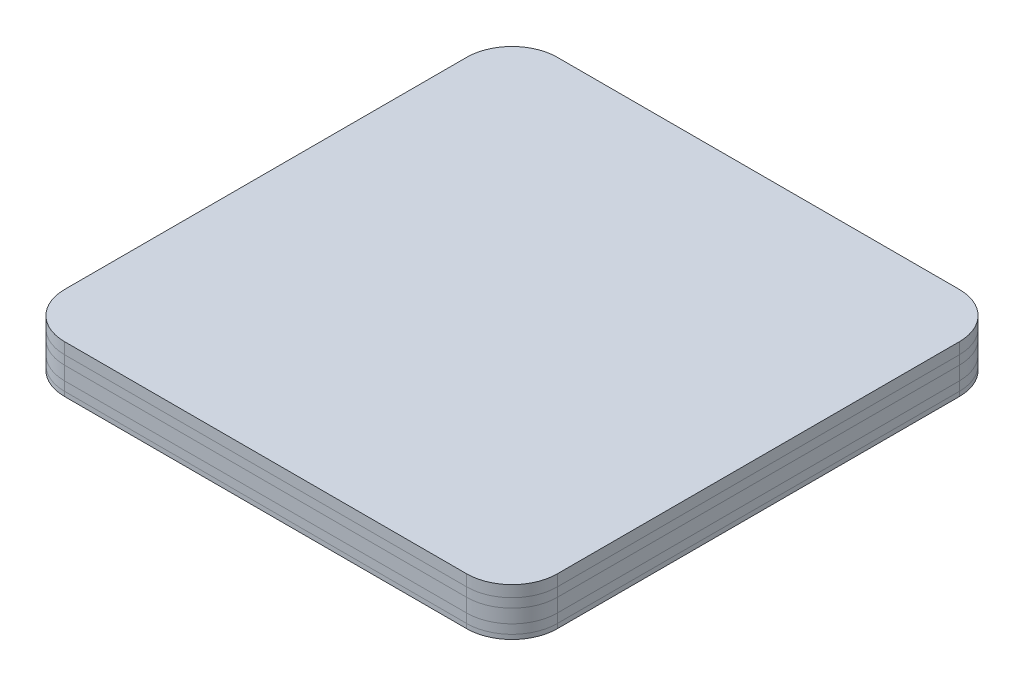
SolidWorks part; units mm, degrees
ref_plane "Front Plane" through (0, 0, 0) normal (0, 0, 1) x (1, 0, 0)
ref_plane "Top Plane" through (0, 0, 0) normal (0, 1, 0) x (1, 0, 0)
ref_plane "Right Plane" through (0, 0, 0) normal (1, 0, 0) x (0, 0, -1)
sketch "Sketch1" plane through (0, 0, 0) normal (0, 1, 0) x (1, 0, 0)
  line L8 (-54.4, 44.4) -> (-54.4, -44.4)
  line L9 (-44.4, -54.4) -> (44.4, -54.4)
  line L10 (54.4, -44.4) -> (54.4, 44.4)
  line L11 (44.4, 54.4) -> (-44.4, 54.4)
  line L12 (-53.4, -44.4) -> (-53.4, 44.4)
  line L13 (-44.4, -53.4) -> (44.4, -53.4)
  line L14 (53.4, -44.4) -> (53.4, 44.4)
  line L15 (-44.4, 53.4) -> (44.4, 53.4)
  arc A8 (-44.4, 54.4) -> (-54.4, 44.4) centre (-44.4, 44.4) ccw
  arc A9 (-54.4, -44.4) -> (-44.4, -54.4) centre (-44.4, -44.4) ccw
  arc A10 (44.4, -54.4) -> (54.4, -44.4) centre (44.4, -44.4) ccw
  arc A11 (54.4, 44.4) -> (44.4, 54.4) centre (44.4, 44.4) ccw
  arc A12 (-53.4, -44.4) -> (-44.4, -53.4) centre (-44.4, -44.4) ccw
  arc A13 (44.4, -53.4) -> (53.4, -44.4) centre (44.4, -44.4) ccw
  arc A14 (53.4, 44.4) -> (44.4, 53.4) centre (44.4, 44.4) ccw
  arc A15 (-44.4, 53.4) -> (-53.4, 44.4) centre (-44.4, 44.4) ccw
sketch "Sketch2" plane through (0, 0, 0) normal (0, 1, 0) x (1, 0, 0)
  line L13 (44.4, 51.9) -> (-44.4, 51.9)
  line L14 (51.9, -44.4) -> (51.9, 44.4)
  line L15 (-44.4, -51.9) -> (44.4, -51.9)
  line L16 (-51.9, 44.4) -> (-51.9, -44.4)
  line L17 (44.4, 51.9) -> (-44.4, 51.9)
  line L18 (51.9, -44.4) -> (51.9, 44.4)
  line L19 (-44.4, -51.9) -> (44.4, -51.9)
  line L20 (-51.9, 44.4) -> (-51.9, -44.4)
  line L25 (44.4, 52.9) -> (-44.4, 52.9)
  line L26 (52.9, -44.4) -> (52.9, 44.4)
  line L27 (-44.4, -52.9) -> (44.4, -52.9)
  line L28 (-52.9, 44.4) -> (-52.9, -44.4)
  line L29 (44.4, 52.9) -> (-44.4, 52.9)
  line L30 (52.9, -44.4) -> (52.9, 44.4)
  line L31 (-44.4, -52.9) -> (44.4, -52.9)
  line L32 (-52.9, 44.4) -> (-52.9, -44.4)
  arc A13 (51.9, 44.4) -> (44.4, 51.9) centre (44.4, 44.4) ccw
  arc A14 (44.4, -51.9) -> (51.9, -44.4) centre (44.4, -44.4) ccw
  arc A15 (-51.9, -44.4) -> (-44.4, -51.9) centre (-44.4, -44.4) ccw
  arc A16 (-44.4, 51.9) -> (-51.9, 44.4) centre (-44.4, 44.4) ccw
  arc A17 (51.9, 44.4) -> (44.4, 51.9) centre (44.4, 44.4) ccw
  arc A18 (44.4, -51.9) -> (51.9, -44.4) centre (44.4, -44.4) ccw
  arc A19 (-51.9, -44.4) -> (-44.4, -51.9) centre (-44.4, -44.4) ccw
  arc A20 (-44.4, 51.9) -> (-51.9, 44.4) centre (-44.4, 44.4) ccw
  arc A25 (52.9, 44.4) -> (44.4, 52.9) centre (44.4, 44.4) ccw
  arc A26 (44.4, -52.9) -> (52.9, -44.4) centre (44.4, -44.4) ccw
  arc A27 (-52.9, -44.4) -> (-44.4, -52.9) centre (-44.4, -44.4) ccw
  arc A28 (-44.4, 52.9) -> (-52.9, 44.4) centre (-44.4, 44.4) ccw
  arc A29 (52.9, 44.4) -> (44.4, 52.9) centre (44.4, 44.4) ccw
  arc A30 (44.4, -52.9) -> (52.9, -44.4) centre (44.4, -44.4) ccw
  arc A31 (-52.9, -44.4) -> (-44.4, -52.9) centre (-44.4, -44.4) ccw
  arc A32 (-44.4, 52.9) -> (-52.9, 44.4) centre (-44.4, 44.4) ccw
  dimension "D1" = 1.5
  dimension "D2" = 0.5
extrude "Boss-Extrude1" add sketch "Sketch2" against normal blind 0.1
extrude "Boss-Extrude2" add sketch "Sketch1" along normal blind 1 from surface contours L15 A15 L12 A12 L13 A13 L14 A14 | L10 A11 L11 A8 L8 A9 L9 A10 A15 L15 A14 L14 A13 L13 A12 L12 region at (-51.3623, 0, -51.3623) region at (0, 0, 0) starting at face at (0, -0.1, 0)
sketch "Sketch3" plane through (0, -0.1, 0) normal (0, -1, 0) x (1, 0, 0)
  line L4 (-44.4, -53.4) -> (44.4, -53.4)
  line L5 (-53.4, 44.4) -> (-53.4, -44.4)
  line L6 (-63.6932, 3.6619) -> (-60.3935, 9.2624)
  line L7 (-70.1932, 3.7193) -> (-63.6932, 3.6619)
  line L8 (-73.3935, 9.3771) -> (-70.1932, 3.7193)
  line L9 (-70.0938, 14.9776) -> (-73.3935, 9.3771)
  line L10 (-63.5938, 14.9203) -> (-70.0938, 14.9776)
  line L11 (-60.3935, 9.2624) -> (-63.5938, 14.9203)
  line L12 (-63.6932, 3.6619) -> (-60.3935, 9.2624)
  line L13 (-70.1932, 3.7193) -> (-63.6932, 3.6619)
  line L14 (-73.3935, 9.3771) -> (-70.1932, 3.7193)
  line L15 (-70.0938, 14.9776) -> (-73.3935, 9.3771)
  line L16 (-63.5938, 14.9203) -> (-70.0938, 14.9776)
  line L17 (-60.3935, 9.2624) -> (-63.5938, 14.9203)
  line L18 (22.3868, 40.4419) -> (25.6865, 46.0424)
  line L19 (15.8868, 40.4993) -> (22.3868, 40.4419)
  line L20 (12.6865, 46.1571) -> (15.8868, 40.4993)
  line L21 (15.9862, 51.7576) -> (12.6865, 46.1571)
  line L22 (22.4862, 51.7003) -> (15.9862, 51.7576)
  line L23 (25.6865, 46.0424) -> (22.4862, 51.7003)
  line L24 (22.3868, 40.4419) -> (25.6865, 46.0424)
  line L25 (15.8868, 40.4993) -> (22.3868, 40.4419)
  line L26 (12.6865, 46.1571) -> (15.8868, 40.4993)
  line L27 (15.9862, 51.7576) -> (12.6865, 46.1571)
  line L28 (22.4862, 51.7003) -> (15.9862, 51.7576)
  line L29 (25.6865, 46.0424) -> (22.4862, 51.7003)
  line L30 (33.0043, 34.3119) -> (36.304, 39.9124)
  line L31 (26.5043, 34.3693) -> (33.0043, 34.3119)
  line L32 (23.304, 40.0271) -> (26.5043, 34.3693)
  line L33 (26.6037, 45.6276) -> (23.304, 40.0271)
  line L34 (33.1037, 45.5703) -> (26.6037, 45.6276)
  line L35 (36.304, 39.9124) -> (33.1037, 45.5703)
  line L36 (33.0043, 34.3119) -> (36.304, 39.9124)
  line L37 (26.5043, 34.3693) -> (33.0043, 34.3119)
  line L38 (23.304, 40.0271) -> (26.5043, 34.3693)
  line L39 (26.6037, 45.6276) -> (23.304, 40.0271)
  line L40 (33.1037, 45.5703) -> (26.6037, 45.6276)
  line L41 (36.304, 39.9124) -> (33.1037, 45.5703)
  line L42 (22.3868, -20.8581) -> (25.6865, -15.2576)
  line L43 (15.8868, -20.8007) -> (22.3868, -20.8581)
  line L44 (12.6865, -15.1429) -> (15.8868, -20.8007)
  line L45 (15.9862, -9.5424) -> (12.6865, -15.1429)
  line L46 (22.4862, -9.5997) -> (15.9862, -9.5424)
  line L47 (25.6865, -15.2576) -> (22.4862, -9.5997)
  line L48 (22.3868, -20.8581) -> (25.6865, -15.2576)
  line L49 (15.8868, -20.8007) -> (22.3868, -20.8581)
  line L50 (12.6865, -15.1429) -> (15.8868, -20.8007)
  line L51 (15.9862, -9.5424) -> (12.6865, -15.1429)
  line L52 (22.4862, -9.5997) -> (15.9862, -9.5424)
  line L53 (25.6865, -15.2576) -> (22.4862, -9.5997)
  line L54 (33.0043, -26.9881) -> (36.304, -21.3876)
  line L55 (26.5043, -26.9307) -> (33.0043, -26.9881)
  line L56 (23.304, -21.2729) -> (26.5043, -26.9307)
  line L57 (26.6037, -15.6724) -> (23.304, -21.2729)
  line L58 (33.1037, -15.7297) -> (26.6037, -15.6724)
  line L59 (36.304, -21.3876) -> (33.1037, -15.7297)
  line L60 (33.0043, -26.9881) -> (36.304, -21.3876)
  line L61 (26.5043, -26.9307) -> (33.0043, -26.9881)
  line L62 (23.304, -21.2729) -> (26.5043, -26.9307)
  line L63 (26.6037, -15.6724) -> (23.304, -21.2729)
  line L64 (33.1037, -15.7297) -> (26.6037, -15.6724)
  line L65 (36.304, -21.3876) -> (33.1037, -15.7297)
  line L66 (-42.1732, -33.1181) -> (-38.8735, -27.5176)
  line L67 (-48.6732, -33.0607) -> (-42.1732, -33.1181)
  line L68 (-51.8735, -27.4029) -> (-48.6732, -33.0607)
  line L69 (-48.5738, -21.8024) -> (-51.8735, -27.4029)
  line L70 (-42.0738, -21.8597) -> (-48.5738, -21.8024)
  line L71 (-38.8735, -27.5176) -> (-42.0738, -21.8597)
  line L72 (-42.1732, -33.1181) -> (-38.8735, -27.5176)
  line L73 (-48.6732, -33.0607) -> (-42.1732, -33.1181)
  line L74 (-51.8735, -27.4029) -> (-48.6732, -33.0607)
  line L75 (-48.5738, -21.8024) -> (-51.8735, -27.4029)
  line L76 (-42.0738, -21.8597) -> (-48.5738, -21.8024)
  line L77 (-38.8735, -27.5176) -> (-42.0738, -21.8597)
  line L78 (-31.5557, -39.2481) -> (-28.256, -33.6476)
  line L79 (-38.0557, -39.1907) -> (-31.5557, -39.2481)
  line L80 (-41.256, -33.5329) -> (-38.0557, -39.1907)
  line L81 (-37.9563, -27.9324) -> (-41.256, -33.5329)
  line L82 (-31.4563, -27.9897) -> (-37.9563, -27.9324)
  line L83 (-28.256, -33.6476) -> (-31.4563, -27.9897)
  line L84 (-31.5557, -39.2481) -> (-28.256, -33.6476)
  line L85 (-38.0557, -39.1907) -> (-31.5557, -39.2481)
  line L86 (-41.256, -33.5329) -> (-38.0557, -39.1907)
  line L87 (-37.9563, -27.9324) -> (-41.256, -33.5329)
  line L88 (-31.4563, -27.9897) -> (-37.9563, -27.9324)
  line L89 (-28.256, -33.6476) -> (-31.4563, -27.9897)
  line L90 (-59.5757, -2.4107) -> (-53.0757, -2.4681)
  line L91 (-62.776, 3.2471) -> (-59.5757, -2.4107)
  line L92 (-59.4763, 8.8476) -> (-62.776, 3.2471)
  line L93 (-52.9763, 8.7903) -> (-59.4763, 8.8476)
  line L94 (-49.776, 3.1324) -> (-52.9763, 8.7903)
  line L95 (-53.0757, -2.4681) -> (-49.776, 3.1324)
  line L96 (-59.5757, -2.4107) -> (-53.0757, -2.4681)
  line L97 (-62.776, 3.2471) -> (-59.5757, -2.4107)
  line L98 (-59.4763, 8.8476) -> (-62.776, 3.2471)
  line L99 (-52.9763, 8.7903) -> (-59.4763, 8.8476)
  line L100 (-49.776, 3.1324) -> (-52.9763, 8.7903)
  line L101 (-53.0757, -2.4681) -> (-49.776, 3.1324)
  line L102 (22.3868, 28.1819) -> (25.6865, 33.7824)
  line L103 (15.8868, 28.2393) -> (22.3868, 28.1819)
  line L104 (12.6865, 33.8971) -> (15.8868, 28.2393)
  line L105 (15.9862, 39.4976) -> (12.6865, 33.8971)
  line L106 (22.4862, 39.4403) -> (15.9862, 39.4976)
  line L107 (25.6865, 33.7824) -> (22.4862, 39.4403)
  line L108 (22.3868, 28.1819) -> (25.6865, 33.7824)
  line L109 (15.8868, 28.2393) -> (22.3868, 28.1819)
  line L110 (12.6865, 33.8971) -> (15.8868, 28.2393)
  line L111 (15.9862, 39.4976) -> (12.6865, 33.8971)
  line L112 (22.4862, 39.4403) -> (15.9862, 39.4976)
  line L113 (25.6865, 33.7824) -> (22.4862, 39.4403)
  line L114 (33.0043, 22.0519) -> (36.304, 27.6524)
  line L115 (26.5043, 22.1093) -> (33.0043, 22.0519)
  line L116 (23.304, 27.7671) -> (26.5043, 22.1093)
  line L117 (26.6037, 33.3676) -> (23.304, 27.7671)
  line L118 (33.1037, 33.3103) -> (26.6037, 33.3676)
  line L119 (36.304, 27.6524) -> (33.1037, 33.3103)
  line L120 (33.0043, 22.0519) -> (36.304, 27.6524)
  line L121 (26.5043, 22.1093) -> (33.0043, 22.0519)
  line L122 (23.304, 27.7671) -> (26.5043, 22.1093)
  line L123 (26.6037, 33.3676) -> (23.304, 27.7671)
  line L124 (33.1037, 33.3103) -> (26.6037, 33.3676)
  line L125 (36.304, 27.6524) -> (33.1037, 33.3103)
  line L126 (43.9068, -8.5981) -> (47.2065, -2.9976)
  line L127 (37.4068, -8.5407) -> (43.9068, -8.5981)
  line L128 (34.2065, -2.8829) -> (37.4068, -8.5407)
  line L129 (37.5062, 2.7176) -> (34.2065, -2.8829)
  line L130 (44.0062, 2.6603) -> (37.5062, 2.7176)
  line L131 (47.2065, -2.9976) -> (44.0062, 2.6603)
  line L132 (43.9068, -8.5981) -> (47.2065, -2.9976)
  line L133 (37.4068, -8.5407) -> (43.9068, -8.5981)
  line L134 (34.2065, -2.8829) -> (37.4068, -8.5407)
  line L135 (37.5062, 2.7176) -> (34.2065, -2.8829)
  line L136 (44.0062, 2.6603) -> (37.5062, 2.7176)
  line L137 (47.2065, -2.9976) -> (44.0062, 2.6603)
  line L138 (-42.1732, -45.3781) -> (-38.8735, -39.7776)
  line L139 (-48.6732, -45.3207) -> (-42.1732, -45.3781)
  line L140 (-51.8735, -39.6629) -> (-48.6732, -45.3207)
  line L141 (-48.5738, -34.0624) -> (-51.8735, -39.6629)
  line L142 (-42.0738, -34.1197) -> (-48.5738, -34.0624)
  line L143 (-38.8735, -39.7776) -> (-42.0738, -34.1197)
  line L144 (-42.1732, -45.3781) -> (-38.8735, -39.7776)
  line L145 (-48.6732, -45.3207) -> (-42.1732, -45.3781)
  line L146 (-51.8735, -39.6629) -> (-48.6732, -45.3207)
  line L147 (-48.5738, -34.0624) -> (-51.8735, -39.6629)
  line L148 (-42.0738, -34.1197) -> (-48.5738, -34.0624)
  line L149 (-38.8735, -39.7776) -> (-42.0738, -34.1197)
  line L150 (-59.5757, 34.3693) -> (-53.0757, 34.3119)
  line L151 (-62.776, 40.0271) -> (-59.5757, 34.3693)
  line L152 (-59.4763, 45.6276) -> (-62.776, 40.0271)
  line L153 (-52.9763, 45.5703) -> (-59.4763, 45.6276)
  line L154 (-49.776, 39.9124) -> (-52.9763, 45.5703)
  line L155 (-53.0757, 34.3119) -> (-49.776, 39.9124)
  line L156 (-59.5757, 34.3693) -> (-53.0757, 34.3119)
  line L157 (-62.776, 40.0271) -> (-59.5757, 34.3693)
  line L158 (-59.4763, 45.6276) -> (-62.776, 40.0271)
  line L159 (-52.9763, 45.5703) -> (-59.4763, 45.6276)
  line L160 (-49.776, 39.9124) -> (-52.9763, 45.5703)
  line L161 (-53.0757, 34.3119) -> (-49.776, 39.9124)
  line L162 (-63.5938, 51.7003) -> (-70.0938, 51.7576)
  line L163 (-70.0938, 51.7576) -> (-73.3935, 46.1571)
  line L164 (-73.3935, 46.1571) -> (-70.1932, 40.4993)
  line L165 (-70.1932, 40.4993) -> (-63.6932, 40.4419)
  line L166 (-63.6932, 40.4419) -> (-60.3935, 46.0424)
  line L167 (-60.3935, 46.0424) -> (-63.5938, 51.7003)
  line L168 (-63.5938, 51.7003) -> (-70.0938, 51.7576)
  line L169 (-70.0938, 51.7576) -> (-73.3935, 46.1571)
  line L170 (-73.3935, 46.1571) -> (-70.1932, 40.4993)
  line L171 (-70.1932, 40.4993) -> (-63.6932, 40.4419)
  line L172 (-63.6932, 40.4419) -> (-60.3935, 46.0424)
  line L173 (-60.3935, 46.0424) -> (-63.5938, 51.7003)
  line L174 (43.9068, 40.4419) -> (47.2065, 46.0424)
  line L175 (37.4068, 40.4993) -> (43.9068, 40.4419)
  line L176 (34.2065, 46.1571) -> (37.4068, 40.4993)
  line L177 (37.5062, 51.7576) -> (34.2065, 46.1571)
  line L178 (44.0062, 51.7003) -> (37.5062, 51.7576)
  line L179 (47.2065, 46.0424) -> (44.0062, 51.7003)
  line L180 (43.9068, 40.4419) -> (47.2065, 46.0424)
  line L181 (37.4068, 40.4993) -> (43.9068, 40.4419)
  line L182 (34.2065, 46.1571) -> (37.4068, 40.4993)
  line L183 (37.5062, 51.7576) -> (34.2065, 46.1571)
  line L184 (44.0062, 51.7003) -> (37.5062, 51.7576)
  line L185 (47.2065, 46.0424) -> (44.0062, 51.7003)
  line L186 (43.9068, -20.8581) -> (47.2065, -15.2576)
  line L187 (37.4068, -20.8007) -> (43.9068, -20.8581)
  line L188 (34.2065, -15.1429) -> (37.4068, -20.8007)
  line L189 (37.5062, -9.5424) -> (34.2065, -15.1429)
  line L190 (44.0062, -9.5997) -> (37.5062, -9.5424)
  line L191 (47.2065, -15.2576) -> (44.0062, -9.5997)
  line L192 (43.9068, -20.8581) -> (47.2065, -15.2576)
  line L193 (37.4068, -20.8007) -> (43.9068, -20.8581)
  line L194 (34.2065, -15.1429) -> (37.4068, -20.8007)
  line L195 (37.5062, -9.5424) -> (34.2065, -15.1429)
  line L196 (44.0062, -9.5997) -> (37.5062, -9.5424)
  line L197 (47.2065, -15.2576) -> (44.0062, -9.5997)
  line L198 (54.6237, -3.4697) -> (48.1237, -3.4124)
  line L199 (57.824, -9.1276) -> (54.6237, -3.4697)
  line L200 (54.5243, -14.7281) -> (57.824, -9.1276)
  line L201 (48.0243, -14.6707) -> (54.5243, -14.7281)
  line L202 (44.824, -9.0129) -> (48.0243, -14.6707)
  line L203 (48.1237, -3.4124) -> (44.824, -9.0129)
  line L204 (54.6237, -3.4697) -> (48.1237, -3.4124)
  line L205 (57.824, -9.1276) -> (54.6237, -3.4697)
  line L206 (54.5243, -14.7281) -> (57.824, -9.1276)
  line L207 (48.0243, -14.6707) -> (54.5243, -14.7281)
  line L208 (44.824, -9.0129) -> (48.0243, -14.6707)
  line L209 (48.1237, -3.4124) -> (44.824, -9.0129)
  line L210 (-20.6532, -33.1181) -> (-17.3535, -27.5176)
  line L211 (-27.1532, -33.0607) -> (-20.6532, -33.1181)
  line L212 (-30.3535, -27.4029) -> (-27.1532, -33.0607)
  line L213 (-27.0538, -21.8024) -> (-30.3535, -27.4029)
  line L214 (-20.5538, -21.8597) -> (-27.0538, -21.8024)
  line L215 (-17.3535, -27.5176) -> (-20.5538, -21.8597)
  line L216 (-20.6532, -33.1181) -> (-17.3535, -27.5176)
  line L217 (-27.1532, -33.0607) -> (-20.6532, -33.1181)
  line L218 (-30.3535, -27.4029) -> (-27.1532, -33.0607)
  line L219 (-27.0538, -21.8024) -> (-30.3535, -27.4029)
  line L220 (-20.5538, -21.8597) -> (-27.0538, -21.8024)
  line L221 (-17.3535, -27.5176) -> (-20.5538, -21.8597)
  line L222 (-31.4563, -40.2497) -> (-37.9563, -40.1924)
  line L223 (-28.256, -45.9076) -> (-31.4563, -40.2497)
  line L224 (-31.5557, -51.5081) -> (-28.256, -45.9076)
  line L225 (-38.0557, -51.4507) -> (-31.5557, -51.5081)
  line L226 (-41.256, -45.7929) -> (-38.0557, -51.4507)
  line L227 (-37.9563, -40.1924) -> (-41.256, -45.7929)
  line L228 (-31.4563, -40.2497) -> (-37.9563, -40.1924)
  line L229 (-28.256, -45.9076) -> (-31.4563, -40.2497)
  line L230 (-31.5557, -51.5081) -> (-28.256, -45.9076)
  line L231 (-38.0557, -51.4507) -> (-31.5557, -51.5081)
  line L232 (-41.256, -45.7929) -> (-38.0557, -51.4507)
  line L233 (-37.9563, -40.1924) -> (-41.256, -45.7929)
  line L234 (-59.5757, 22.1093) -> (-53.0757, 22.0519)
  line L235 (-62.776, 27.7671) -> (-59.5757, 22.1093)
  line L236 (-59.4763, 33.3676) -> (-62.776, 27.7671)
  line L237 (-52.9763, 33.3103) -> (-59.4763, 33.3676)
  line L238 (-49.776, 27.6524) -> (-52.9763, 33.3103)
  line L239 (-53.0757, 22.0519) -> (-49.776, 27.6524)
  line L240 (-59.5757, 22.1093) -> (-53.0757, 22.0519)
  line L241 (-62.776, 27.7671) -> (-59.5757, 22.1093)
  line L242 (-59.4763, 33.3676) -> (-62.776, 27.7671)
  line L243 (-52.9763, 33.3103) -> (-59.4763, 33.3676)
  line L244 (-49.776, 27.6524) -> (-52.9763, 33.3103)
  line L245 (-53.0757, 22.0519) -> (-49.776, 27.6524)
  line L246 (-70.0938, 39.4976) -> (-73.3935, 33.8971)
  line L247 (-63.5938, 39.4403) -> (-70.0938, 39.4976)
  line L248 (-60.3935, 33.7824) -> (-63.5938, 39.4403)
  line L249 (-63.6932, 28.1819) -> (-60.3935, 33.7824)
  line L250 (-70.1932, 28.2393) -> (-63.6932, 28.1819)
  line L251 (-73.3935, 33.8971) -> (-70.1932, 28.2393)
  line L252 (-70.0938, 39.4976) -> (-73.3935, 33.8971)
  line L253 (-63.5938, 39.4403) -> (-70.0938, 39.4976)
  line L254 (-60.3935, 33.7824) -> (-63.5938, 39.4403)
  line L255 (-63.6932, 28.1819) -> (-60.3935, 33.7824)
  line L256 (-70.1932, 28.2393) -> (-63.6932, 28.1819)
  line L257 (-73.3935, 33.8971) -> (-70.1932, 28.2393)
  line L258 (43.9068, 28.1819) -> (47.2065, 33.7824)
  line L259 (37.4068, 28.2393) -> (43.9068, 28.1819)
  line L260 (34.2065, 33.8971) -> (37.4068, 28.2393)
  line L261 (37.5062, 39.4976) -> (34.2065, 33.8971)
  line L262 (44.0062, 39.4403) -> (37.5062, 39.4976)
  line L263 (47.2065, 33.7824) -> (44.0062, 39.4403)
  line L264 (43.9068, 28.1819) -> (47.2065, 33.7824)
  line L265 (37.4068, 28.2393) -> (43.9068, 28.1819)
  line L266 (34.2065, 33.8971) -> (37.4068, 28.2393)
  line L267 (37.5062, 39.4976) -> (34.2065, 33.8971)
  line L268 (44.0062, 39.4403) -> (37.5062, 39.4976)
  line L269 (47.2065, 33.7824) -> (44.0062, 39.4403)
  line L270 (54.6237, 45.5703) -> (48.1237, 45.6276)
  line L271 (57.824, 39.9124) -> (54.6237, 45.5703)
  line L272 (54.5243, 34.3119) -> (57.824, 39.9124)
  line L273 (48.0243, 34.3693) -> (54.5243, 34.3119)
  line L274 (44.824, 40.0271) -> (48.0243, 34.3693)
  line L275 (48.1237, 45.6276) -> (44.824, 40.0271)
  line L276 (54.6237, 45.5703) -> (48.1237, 45.6276)
  line L277 (57.824, 39.9124) -> (54.6237, 45.5703)
  line L278 (54.5243, 34.3119) -> (57.824, 39.9124)
  line L279 (48.0243, 34.3693) -> (54.5243, 34.3119)
  line L280 (44.824, 40.0271) -> (48.0243, 34.3693)
  line L281 (48.1237, 45.6276) -> (44.824, 40.0271)
  line L282 (-20.6532, 15.9219) -> (-17.3535, 21.5224)
  line L283 (-27.1532, 15.9793) -> (-20.6532, 15.9219)
  line L284 (-30.3535, 21.6371) -> (-27.1532, 15.9793)
  line L285 (-27.0538, 27.2376) -> (-30.3535, 21.6371)
  line L286 (-20.5538, 27.1803) -> (-27.0538, 27.2376)
  line L287 (-17.3535, 21.5224) -> (-20.5538, 27.1803)
  line L288 (-20.6532, 15.9219) -> (-17.3535, 21.5224)
  line L289 (-27.1532, 15.9793) -> (-20.6532, 15.9219)
  line L290 (-30.3535, 21.6371) -> (-27.1532, 15.9793)
  line L291 (-27.0538, 27.2376) -> (-30.3535, 21.6371)
  line L292 (-20.5538, 27.1803) -> (-27.0538, 27.2376)
  line L293 (-17.3535, 21.5224) -> (-20.5538, 27.1803)
  line L294 (44.824, -21.2729) -> (48.0243, -26.9307)
  line L295 (48.1237, -15.6724) -> (44.824, -21.2729)
  line L296 (54.6237, -15.7297) -> (48.1237, -15.6724)
  line L297 (57.824, -21.3876) -> (54.6237, -15.7297)
  line L298 (54.5243, -26.9881) -> (57.824, -21.3876)
  line L299 (48.0243, -26.9307) -> (54.5243, -26.9881)
  line L300 (44.824, -21.2729) -> (48.0243, -26.9307)
  line L301 (48.1237, -15.6724) -> (44.824, -21.2729)
  line L302 (54.6237, -15.7297) -> (48.1237, -15.6724)
  line L303 (57.824, -21.3876) -> (54.6237, -15.7297)
  line L304 (54.5243, -26.9881) -> (57.824, -21.3876)
  line L305 (48.0243, -26.9307) -> (54.5243, -26.9881)
  line L306 (-20.6532, -45.3781) -> (-17.3535, -39.7776)
  line L307 (-27.1532, -45.3207) -> (-20.6532, -45.3781)
  line L308 (-30.3535, -39.6629) -> (-27.1532, -45.3207)
  line L309 (-27.0538, -34.0624) -> (-30.3535, -39.6629)
  line L310 (-20.5538, -34.1197) -> (-27.0538, -34.0624)
  line L311 (-17.3535, -39.7776) -> (-20.5538, -34.1197)
  line L312 (-20.6532, -45.3781) -> (-17.3535, -39.7776)
  line L313 (-27.1532, -45.3207) -> (-20.6532, -45.3781)
  line L314 (-30.3535, -39.6629) -> (-27.1532, -45.3207)
  line L315 (-27.0538, -34.0624) -> (-30.3535, -39.6629)
  line L316 (-20.5538, -34.1197) -> (-27.0538, -34.0624)
  line L317 (-17.3535, -39.7776) -> (-20.5538, -34.1197)
  line L318 (-10.0357, -39.2481) -> (-6.736, -33.6476)
  line L319 (-16.5357, -39.1907) -> (-10.0357, -39.2481)
  line L320 (-19.736, -33.5329) -> (-16.5357, -39.1907)
  line L321 (-16.4363, -27.9324) -> (-19.736, -33.5329)
  line L322 (-9.9363, -27.9897) -> (-16.4363, -27.9324)
  line L323 (-6.736, -33.6476) -> (-9.9363, -27.9897)
  line L324 (-10.0357, -39.2481) -> (-6.736, -33.6476)
  line L325 (-16.5357, -39.1907) -> (-10.0357, -39.2481)
  line L326 (-19.736, -33.5329) -> (-16.5357, -39.1907)
  line L327 (-16.4363, -27.9324) -> (-19.736, -33.5329)
  line L328 (-9.9363, -27.9897) -> (-16.4363, -27.9324)
  line L329 (-6.736, -33.6476) -> (-9.9363, -27.9897)
  line L330 (-27.1532, 53.0193) -> (-20.6532, 52.9619)
  line L331 (-30.3535, 58.6771) -> (-27.1532, 53.0193)
  line L332 (-27.0538, 64.2776) -> (-30.3535, 58.6771)
  line L333 (-20.5538, 64.2203) -> (-27.0538, 64.2776)
  line L334 (-17.3535, 58.5624) -> (-20.5538, 64.2203)
  line L335 (-20.6532, 52.9619) -> (-17.3535, 58.5624)
  line L336 (-27.1532, 53.0193) -> (-20.6532, 52.9619)
  line L337 (-30.3535, 58.6771) -> (-27.1532, 53.0193)
  line L338 (-27.0538, 64.2776) -> (-30.3535, 58.6771)
  line L339 (-20.5538, 64.2203) -> (-27.0538, 64.2776)
  line L340 (-17.3535, 58.5624) -> (-20.5538, 64.2203)
  line L341 (-20.6532, 52.9619) -> (-17.3535, 58.5624)
  line L342 (-10.0357, 46.8319) -> (-6.736, 52.4324)
  line L343 (-16.5357, 46.8893) -> (-10.0357, 46.8319)
  line L344 (-19.736, 52.5471) -> (-16.5357, 46.8893)
  line L345 (-16.4363, 58.1476) -> (-19.736, 52.5471)
  line L346 (-9.9363, 58.0903) -> (-16.4363, 58.1476)
  line L347 (-6.736, 52.4324) -> (-9.9363, 58.0903)
  line L348 (-10.0357, 46.8319) -> (-6.736, 52.4324)
  line L349 (-16.5357, 46.8893) -> (-10.0357, 46.8319)
  line L350 (-19.736, 52.5471) -> (-16.5357, 46.8893)
  line L351 (-16.4363, 58.1476) -> (-19.736, 52.5471)
  line L352 (-9.9363, 58.0903) -> (-16.4363, 58.1476)
  line L353 (-6.736, 52.4324) -> (-9.9363, 58.0903)
  line L354 (-42.1732, -8.5981) -> (-38.8735, -2.9976)
  line L355 (-48.6732, -8.5407) -> (-42.1732, -8.5981)
  line L356 (-51.8735, -2.8829) -> (-48.6732, -8.5407)
  line L357 (-48.5738, 2.7176) -> (-51.8735, -2.8829)
  line L358 (-42.0738, 2.6603) -> (-48.5738, 2.7176)
  line L359 (-38.8735, -2.9976) -> (-42.0738, 2.6603)
  line L360 (-42.1732, -8.5981) -> (-38.8735, -2.9976)
  line L361 (-48.6732, -8.5407) -> (-42.1732, -8.5981)
  line L362 (-51.8735, -2.8829) -> (-48.6732, -8.5407)
  line L363 (-48.5738, 2.7176) -> (-51.8735, -2.8829)
  line L364 (-42.0738, 2.6603) -> (-48.5738, 2.7176)
  line L365 (-38.8735, -2.9976) -> (-42.0738, 2.6603)
  line L366 (44.824, 27.7671) -> (48.0243, 22.1093)
  line L367 (48.1237, 33.3676) -> (44.824, 27.7671)
  line L368 (54.6237, 33.3103) -> (48.1237, 33.3676)
  line L369 (57.824, 27.6524) -> (54.6237, 33.3103)
  line L370 (54.5243, 22.0519) -> (57.824, 27.6524)
  line L371 (48.0243, 22.1093) -> (54.5243, 22.0519)
  line L372 (44.824, 27.7671) -> (48.0243, 22.1093)
  line L373 (48.1237, 33.3676) -> (44.824, 27.7671)
  line L374 (54.6237, 33.3103) -> (48.1237, 33.3676)
  line L375 (57.824, 27.6524) -> (54.6237, 33.3103)
  line L376 (54.5243, 22.0519) -> (57.824, 27.6524)
  line L377 (48.0243, 22.1093) -> (54.5243, 22.0519)
  line L378 (-20.6532, 3.6619) -> (-17.3535, 9.2624)
  line L379 (-27.1532, 3.7193) -> (-20.6532, 3.6619)
  line L380 (-30.3535, 9.3771) -> (-27.1532, 3.7193)
  line L381 (-27.0538, 14.9776) -> (-30.3535, 9.3771)
  line L382 (-20.5538, 14.9203) -> (-27.0538, 14.9776)
  line L383 (-17.3535, 9.2624) -> (-20.5538, 14.9203)
  line L384 (-20.6532, 3.6619) -> (-17.3535, 9.2624)
  line L385 (-27.1532, 3.7193) -> (-20.6532, 3.6619)
  line L386 (-30.3535, 9.3771) -> (-27.1532, 3.7193)
  line L387 (-27.0538, 14.9776) -> (-30.3535, 9.3771)
  line L388 (-20.5538, 14.9203) -> (-27.0538, 14.9776)
  line L389 (-17.3535, 9.2624) -> (-20.5538, 14.9203)
  line L390 (-10.0357, 9.7919) -> (-6.736, 15.3924)
  line L391 (-16.5357, 9.8493) -> (-10.0357, 9.7919)
  line L392 (-19.736, 15.5071) -> (-16.5357, 9.8493)
  line L393 (-16.4363, 21.1076) -> (-19.736, 15.5071)
  line L394 (-9.9363, 21.0503) -> (-16.4363, 21.1076)
  line L395 (-6.736, 15.3924) -> (-9.9363, 21.0503)
  line L396 (-10.0357, 9.7919) -> (-6.736, 15.3924)
  line L397 (-16.5357, 9.8493) -> (-10.0357, 9.7919)
  line L398 (-19.736, 15.5071) -> (-16.5357, 9.8493)
  line L399 (-16.4363, 21.1076) -> (-19.736, 15.5071)
  line L400 (-9.9363, 21.0503) -> (-16.4363, 21.1076)
  line L401 (-6.736, 15.3924) -> (-9.9363, 21.0503)
  line L402 (-10.0357, -51.5081) -> (-6.736, -45.9076)
  line L403 (-16.5357, -51.4507) -> (-10.0357, -51.5081)
  line L404 (-19.736, -45.7929) -> (-16.5357, -51.4507)
  line L405 (-16.4363, -40.1924) -> (-19.736, -45.7929)
  line L406 (-9.9363, -40.2497) -> (-16.4363, -40.1924)
  line L407 (-6.736, -45.9076) -> (-9.9363, -40.2497)
  line L408 (-10.0357, -51.5081) -> (-6.736, -45.9076)
  line L409 (-16.5357, -51.4507) -> (-10.0357, -51.5081)
  line L410 (-19.736, -45.7929) -> (-16.5357, -51.4507)
  line L411 (-16.4363, -40.1924) -> (-19.736, -45.7929)
  line L412 (-9.9363, -40.2497) -> (-16.4363, -40.1924)
  line L413 (-6.736, -45.9076) -> (-9.9363, -40.2497)
  line L414 (0.8668, 52.9619) -> (4.1665, 58.5624)
  line L415 (-5.6332, 53.0193) -> (0.8668, 52.9619)
  line L416 (-8.8335, 58.6771) -> (-5.6332, 53.0193)
  line L417 (-5.5338, 64.2776) -> (-8.8335, 58.6771)
  line L418 (0.9662, 64.2203) -> (-5.5338, 64.2776)
  line L419 (4.1665, 58.5624) -> (0.9662, 64.2203)
  line L420 (0.8668, 52.9619) -> (4.1665, 58.5624)
  line L421 (-5.6332, 53.0193) -> (0.8668, 52.9619)
  line L422 (-8.8335, 58.6771) -> (-5.6332, 53.0193)
  line L423 (-5.5338, 64.2776) -> (-8.8335, 58.6771)
  line L424 (0.9662, 64.2203) -> (-5.5338, 64.2776)
  line L425 (4.1665, 58.5624) -> (0.9662, 64.2203)
  line L426 (11.4843, 46.8319) -> (14.784, 52.4324)
  line L427 (4.9843, 46.8893) -> (11.4843, 46.8319)
  line L428 (1.784, 52.5471) -> (4.9843, 46.8893)
  line L429 (5.0837, 58.1476) -> (1.784, 52.5471)
  line L430 (11.5837, 58.0903) -> (5.0837, 58.1476)
  line L431 (14.784, 52.4324) -> (11.5837, 58.0903)
  line L432 (11.4843, 46.8319) -> (14.784, 52.4324)
  line L433 (4.9843, 46.8893) -> (11.4843, 46.8319)
  line L434 (1.784, 52.5471) -> (4.9843, 46.8893)
  line L435 (5.0837, 58.1476) -> (1.784, 52.5471)
  line L436 (11.5837, 58.0903) -> (5.0837, 58.1476)
  line L437 (14.784, 52.4324) -> (11.5837, 58.0903)
  line L438 (-42.1732, -20.8581) -> (-38.8735, -15.2576)
  line L439 (-48.6732, -20.8007) -> (-42.1732, -20.8581)
  line L440 (-51.8735, -15.1429) -> (-48.6732, -20.8007)
  line L441 (-48.5738, -9.5424) -> (-51.8735, -15.1429)
  line L442 (-42.0738, -9.5997) -> (-48.5738, -9.5424)
  line L443 (-38.8735, -15.2576) -> (-42.0738, -9.5997)
  line L444 (-42.1732, -20.8581) -> (-38.8735, -15.2576)
  line L445 (-48.6732, -20.8007) -> (-42.1732, -20.8581)
  line L446 (-51.8735, -15.1429) -> (-48.6732, -20.8007)
  line L447 (-48.5738, -9.5424) -> (-51.8735, -15.1429)
  line L448 (-42.0738, -9.5997) -> (-48.5738, -9.5424)
  line L449 (-38.8735, -15.2576) -> (-42.0738, -9.5997)
  line L450 (-31.5557, -14.7281) -> (-28.256, -9.1276)
  line L451 (-38.0557, -14.6707) -> (-31.5557, -14.7281)
  line L452 (-41.256, -9.0129) -> (-38.0557, -14.6707)
  line L453 (-37.9563, -3.4124) -> (-41.256, -9.0129)
  line L454 (-31.4563, -3.4697) -> (-37.9563, -3.4124)
  line L455 (-28.256, -9.1276) -> (-31.4563, -3.4697)
  line L456 (-31.5557, -14.7281) -> (-28.256, -9.1276)
  line L457 (-38.0557, -14.6707) -> (-31.5557, -14.7281)
  line L458 (-41.256, -9.0129) -> (-38.0557, -14.6707)
  line L459 (-37.9563, -3.4124) -> (-41.256, -9.0129)
  line L460 (-31.4563, -3.4697) -> (-37.9563, -3.4124)
  line L461 (-28.256, -9.1276) -> (-31.4563, -3.4697)
  line L462 (-10.0357, -2.4681) -> (-6.736, 3.1324)
  line L463 (-16.5357, -2.4107) -> (-10.0357, -2.4681)
  line L464 (-19.736, 3.2471) -> (-16.5357, -2.4107)
  line L465 (-16.4363, 8.8476) -> (-19.736, 3.2471)
  line L466 (-9.9363, 8.7903) -> (-16.4363, 8.8476)
  line L467 (-6.736, 3.1324) -> (-9.9363, 8.7903)
  line L468 (-10.0357, -2.4681) -> (-6.736, 3.1324)
  line L469 (-16.5357, -2.4107) -> (-10.0357, -2.4681)
  line L470 (-19.736, 3.2471) -> (-16.5357, -2.4107)
  line L471 (-16.4363, 8.8476) -> (-19.736, 3.2471)
  line L472 (-9.9363, 8.7903) -> (-16.4363, 8.8476)
  line L473 (-6.736, 3.1324) -> (-9.9363, 8.7903)
  line L474 (0.9662, -21.8597) -> (-5.5338, -21.8024)
  line L475 (4.1665, -27.5176) -> (0.9662, -21.8597)
  line L476 (0.8668, -33.1181) -> (4.1665, -27.5176)
  line L477 (-5.6332, -33.0607) -> (0.8668, -33.1181)
  line L478 (-8.8335, -27.4029) -> (-5.6332, -33.0607)
  line L479 (-5.5338, -21.8024) -> (-8.8335, -27.4029)
  line L480 (0.9662, -21.8597) -> (-5.5338, -21.8024)
  line L481 (4.1665, -27.5176) -> (0.9662, -21.8597)
  line L482 (0.8668, -33.1181) -> (4.1665, -27.5176)
  line L483 (-5.6332, -33.0607) -> (0.8668, -33.1181)
  line L484 (-8.8335, -27.4029) -> (-5.6332, -33.0607)
  line L485 (-5.5338, -21.8024) -> (-8.8335, -27.4029)
  line L486 (11.4843, -39.2481) -> (14.784, -33.6476)
  line L487 (4.9843, -39.1907) -> (11.4843, -39.2481)
  line L488 (1.784, -33.5329) -> (4.9843, -39.1907)
  line L489 (5.0837, -27.9324) -> (1.784, -33.5329)
  line L490 (11.5837, -27.9897) -> (5.0837, -27.9324)
  line L491 (14.784, -33.6476) -> (11.5837, -27.9897)
  line L492 (11.4843, -39.2481) -> (14.784, -33.6476)
  line L493 (4.9843, -39.1907) -> (11.4843, -39.2481)
  line L494 (1.784, -33.5329) -> (4.9843, -39.1907)
  line L495 (5.0837, -27.9324) -> (1.784, -33.5329)
  line L496 (11.5837, -27.9897) -> (5.0837, -27.9324)
  line L497 (14.784, -33.6476) -> (11.5837, -27.9897)
  line L498 (22.3868, 52.9619) -> (25.6865, 58.5624)
  line L499 (15.8868, 53.0193) -> (22.3868, 52.9619)
  line L500 (12.6865, 58.6771) -> (15.8868, 53.0193)
  line L501 (15.9862, 64.2776) -> (12.6865, 58.6771)
  line L502 (22.4862, 64.2203) -> (15.9862, 64.2776)
  line L503 (25.6865, 58.5624) -> (22.4862, 64.2203)
  line L504 (22.3868, 52.9619) -> (25.6865, 58.5624)
  line L505 (15.8868, 53.0193) -> (22.3868, 52.9619)
  line L506 (12.6865, 58.6771) -> (15.8868, 53.0193)
  line L507 (15.9862, 64.2776) -> (12.6865, 58.6771)
  line L508 (22.4862, 64.2203) -> (15.9862, 64.2776)
  line L509 (25.6865, 58.5624) -> (22.4862, 64.2203)
  line L510 (-31.5557, -26.9881) -> (-28.256, -21.3876)
  line L511 (-38.0557, -26.9307) -> (-31.5557, -26.9881)
  line L512 (-41.256, -21.2729) -> (-38.0557, -26.9307)
  line L513 (-37.9563, -15.6724) -> (-41.256, -21.2729)
  line L514 (-31.4563, -15.7297) -> (-37.9563, -15.6724)
  line L515 (-28.256, -21.3876) -> (-31.4563, -15.7297)
  line L516 (-31.5557, -26.9881) -> (-28.256, -21.3876)
  line L517 (-38.0557, -26.9307) -> (-31.5557, -26.9881)
  line L518 (-41.256, -21.2729) -> (-38.0557, -26.9307)
  line L519 (-37.9563, -15.6724) -> (-41.256, -21.2729)
  line L520 (-31.4563, -15.7297) -> (-37.9563, -15.6724)
  line L521 (-28.256, -21.3876) -> (-31.4563, -15.7297)
  line L522 (0.9662, 27.1803) -> (-5.5338, 27.2376)
  line L523 (4.1665, 21.5224) -> (0.9662, 27.1803)
  line L524 (0.8668, 15.9219) -> (4.1665, 21.5224)
  line L525 (-5.6332, 15.9793) -> (0.8668, 15.9219)
  line L526 (-8.8335, 21.6371) -> (-5.6332, 15.9793)
  line L527 (-5.5338, 27.2376) -> (-8.8335, 21.6371)
  line L528 (0.9662, 27.1803) -> (-5.5338, 27.2376)
  line L529 (4.1665, 21.5224) -> (0.9662, 27.1803)
  line L530 (0.8668, 15.9219) -> (4.1665, 21.5224)
  line L531 (-5.6332, 15.9793) -> (0.8668, 15.9219)
  line L532 (-8.8335, 21.6371) -> (-5.6332, 15.9793)
  line L533 (-5.5338, 27.2376) -> (-8.8335, 21.6371)
  line L534 (11.4843, 9.7919) -> (14.784, 15.3924)
  line L535 (4.9843, 9.8493) -> (11.4843, 9.7919)
  line L536 (1.784, 15.5071) -> (4.9843, 9.8493)
  line L537 (5.0837, 21.1076) -> (1.784, 15.5071)
  line L538 (11.5837, 21.0503) -> (5.0837, 21.1076)
  line L539 (14.784, 15.3924) -> (11.5837, 21.0503)
  line L540 (11.4843, 9.7919) -> (14.784, 15.3924)
  line L541 (4.9843, 9.8493) -> (11.4843, 9.7919)
  line L542 (1.784, 15.5071) -> (4.9843, 9.8493)
  line L543 (5.0837, 21.1076) -> (1.784, 15.5071)
  line L544 (11.5837, 21.0503) -> (5.0837, 21.1076)
  line L545 (14.784, 15.3924) -> (11.5837, 21.0503)
  line L546 (-8.8335, -39.6629) -> (-5.6332, -45.3207)
  line L547 (-5.5338, -34.0624) -> (-8.8335, -39.6629)
  line L548 (0.9662, -34.1197) -> (-5.5338, -34.0624)
  line L549 (4.1665, -39.7776) -> (0.9662, -34.1197)
  line L550 (0.8668, -45.3781) -> (4.1665, -39.7776)
  line L551 (-5.6332, -45.3207) -> (0.8668, -45.3781)
  line L552 (-8.8335, -39.6629) -> (-5.6332, -45.3207)
  line L553 (-5.5338, -34.0624) -> (-8.8335, -39.6629)
  line L554 (0.9662, -34.1197) -> (-5.5338, -34.0624)
  line L555 (4.1665, -39.7776) -> (0.9662, -34.1197)
  line L556 (0.8668, -45.3781) -> (4.1665, -39.7776)
  line L557 (-5.6332, -45.3207) -> (0.8668, -45.3781)
  line L558 (11.4843, -51.5081) -> (14.784, -45.9076)
  line L559 (4.9843, -51.4507) -> (11.4843, -51.5081)
  line L560 (1.784, -45.7929) -> (4.9843, -51.4507)
  line L561 (5.0837, -40.1924) -> (1.784, -45.7929)
  line L562 (11.5837, -40.2497) -> (5.0837, -40.1924)
  line L563 (14.784, -45.9076) -> (11.5837, -40.2497)
  line L564 (11.4843, -51.5081) -> (14.784, -45.9076)
  line L565 (4.9843, -51.4507) -> (11.4843, -51.5081)
  line L566 (1.784, -45.7929) -> (4.9843, -51.4507)
  line L567 (5.0837, -40.1924) -> (1.784, -45.7929)
  line L568 (11.5837, -40.2497) -> (5.0837, -40.1924)
  line L569 (14.784, -45.9076) -> (11.5837, -40.2497)
  line L570 (43.9068, 52.9619) -> (47.2065, 58.5624)
  line L571 (37.4068, 53.0193) -> (43.9068, 52.9619)
  line L572 (34.2065, 58.6771) -> (37.4068, 53.0193)
  line L573 (37.5062, 64.2776) -> (34.2065, 58.6771)
  line L574 (44.0062, 64.2203) -> (37.5062, 64.2776)
  line L575 (47.2065, 58.5624) -> (44.0062, 64.2203)
  line L576 (43.9068, 52.9619) -> (47.2065, 58.5624)
  line L577 (37.4068, 53.0193) -> (43.9068, 52.9619)
  line L578 (34.2065, 58.6771) -> (37.4068, 53.0193)
  line L579 (37.5062, 64.2776) -> (34.2065, 58.6771)
  line L580 (44.0062, 64.2203) -> (37.5062, 64.2776)
  line L581 (47.2065, 58.5624) -> (44.0062, 64.2203)
  line L582 (33.1037, 58.0903) -> (26.6037, 58.1476)
  line L583 (26.6037, 58.1476) -> (23.304, 52.5471)
  line L584 (23.304, 52.5471) -> (26.5043, 46.8893)
  line L585 (26.5043, 46.8893) -> (33.0043, 46.8319)
  line L586 (33.0043, 46.8319) -> (36.304, 52.4324)
  line L587 (36.304, 52.4324) -> (33.1037, 58.0903)
  line L588 (33.1037, 58.0903) -> (26.6037, 58.1476)
  line L589 (26.6037, 58.1476) -> (23.304, 52.5471)
  line L590 (23.304, 52.5471) -> (26.5043, 46.8893)
  line L591 (26.5043, 46.8893) -> (33.0043, 46.8319)
  line L592 (33.0043, 46.8319) -> (36.304, 52.4324)
  line L593 (36.304, 52.4324) -> (33.1037, 58.0903)
  line L594 (-42.0738, 27.1803) -> (-48.5738, 27.2376)
  line L595 (-38.8735, 21.5224) -> (-42.0738, 27.1803)
  line L596 (-42.1732, 15.9219) -> (-38.8735, 21.5224)
  line L597 (-48.6732, 15.9793) -> (-42.1732, 15.9219)
  line L598 (-51.8735, 21.6371) -> (-48.6732, 15.9793)
  line L599 (-48.5738, 27.2376) -> (-51.8735, 21.6371)
  line L600 (-42.0738, 27.1803) -> (-48.5738, 27.2376)
  line L601 (-38.8735, 21.5224) -> (-42.0738, 27.1803)
  line L602 (-42.1732, 15.9219) -> (-38.8735, 21.5224)
  line L603 (-48.6732, 15.9793) -> (-42.1732, 15.9219)
  line L604 (-51.8735, 21.6371) -> (-48.6732, 15.9793)
  line L605 (-48.5738, 27.2376) -> (-51.8735, 21.6371)
  line L606 (-31.5557, 9.7919) -> (-28.256, 15.3924)
  line L607 (-38.0557, 9.8493) -> (-31.5557, 9.7919)
  line L608 (-41.256, 15.5071) -> (-38.0557, 9.8493)
  line L609 (-37.9563, 21.1076) -> (-41.256, 15.5071)
  line L610 (-31.4563, 21.0503) -> (-37.9563, 21.1076)
  line L611 (-28.256, 15.3924) -> (-31.4563, 21.0503)
  line L612 (-31.5557, 9.7919) -> (-28.256, 15.3924)
  line L613 (-38.0557, 9.8493) -> (-31.5557, 9.7919)
  line L614 (-41.256, 15.5071) -> (-38.0557, 9.8493)
  line L615 (-37.9563, 21.1076) -> (-41.256, 15.5071)
  line L616 (-31.4563, 21.0503) -> (-37.9563, 21.1076)
  line L617 (-28.256, 15.3924) -> (-31.4563, 21.0503)
  line L618 (-8.8335, 9.3771) -> (-5.6332, 3.7193)
  line L619 (-5.5338, 14.9776) -> (-8.8335, 9.3771)
  line L620 (0.9662, 14.9203) -> (-5.5338, 14.9776)
  line L621 (4.1665, 9.2624) -> (0.9662, 14.9203)
  line L622 (0.8668, 3.6619) -> (4.1665, 9.2624)
  line L623 (-5.6332, 3.7193) -> (0.8668, 3.6619)
  line L624 (-8.8335, 9.3771) -> (-5.6332, 3.7193)
  line L625 (-5.5338, 14.9776) -> (-8.8335, 9.3771)
  line L626 (0.9662, 14.9203) -> (-5.5338, 14.9776)
  line L627 (4.1665, 9.2624) -> (0.9662, 14.9203)
  line L628 (0.8668, 3.6619) -> (4.1665, 9.2624)
  line L629 (-5.6332, 3.7193) -> (0.8668, 3.6619)
  line L630 (11.4843, -2.4681) -> (14.784, 3.1324)
  line L631 (4.9843, -2.4107) -> (11.4843, -2.4681)
  line L632 (1.784, 3.2471) -> (4.9843, -2.4107)
  line L633 (5.0837, 8.8476) -> (1.784, 3.2471)
  line L634 (11.5837, 8.7903) -> (5.0837, 8.8476)
  line L635 (14.784, 3.1324) -> (11.5837, 8.7903)
  line L636 (11.4843, -2.4681) -> (14.784, 3.1324)
  line L637 (4.9843, -2.4107) -> (11.4843, -2.4681)
  line L638 (1.784, 3.2471) -> (4.9843, -2.4107)
  line L639 (5.0837, 8.8476) -> (1.784, 3.2471)
  line L640 (11.5837, 8.7903) -> (5.0837, 8.8476)
  line L641 (14.784, 3.1324) -> (11.5837, 8.7903)
  line L642 (22.3868, -33.1181) -> (25.6865, -27.5176)
  line L643 (15.8868, -33.0607) -> (22.3868, -33.1181)
  line L644 (12.6865, -27.4029) -> (15.8868, -33.0607)
  line L645 (15.9862, -21.8024) -> (12.6865, -27.4029)
  line L646 (22.4862, -21.8597) -> (15.9862, -21.8024)
  line L647 (25.6865, -27.5176) -> (22.4862, -21.8597)
  line L648 (22.3868, -33.1181) -> (25.6865, -27.5176)
  line L649 (15.8868, -33.0607) -> (22.3868, -33.1181)
  line L650 (12.6865, -27.4029) -> (15.8868, -33.0607)
  line L651 (15.9862, -21.8024) -> (12.6865, -27.4029)
  line L652 (22.4862, -21.8597) -> (15.9862, -21.8024)
  line L653 (25.6865, -27.5176) -> (22.4862, -21.8597)
  line L654 (33.0043, -39.2481) -> (36.304, -33.6476)
  line L655 (26.5043, -39.1907) -> (33.0043, -39.2481)
  line L656 (23.304, -33.5329) -> (26.5043, -39.1907)
  line L657 (26.6037, -27.9324) -> (23.304, -33.5329)
  line L658 (33.1037, -27.9897) -> (26.6037, -27.9324)
  line L659 (36.304, -33.6476) -> (33.1037, -27.9897)
  line L660 (33.0043, -39.2481) -> (36.304, -33.6476)
  line L661 (26.5043, -39.1907) -> (33.0043, -39.2481)
  line L662 (23.304, -33.5329) -> (26.5043, -39.1907)
  line L663 (26.6037, -27.9324) -> (23.304, -33.5329)
  line L664 (33.1037, -27.9897) -> (26.6037, -27.9324)
  line L665 (36.304, -33.6476) -> (33.1037, -27.9897)
  line L666 (-42.1732, 52.9619) -> (-38.8735, 58.5624)
  line L667 (-48.6732, 53.0193) -> (-42.1732, 52.9619)
  line L668 (-51.8735, 58.6771) -> (-48.6732, 53.0193)
  line L669 (-48.5738, 64.2776) -> (-51.8735, 58.6771)
  line L670 (-42.0738, 64.2203) -> (-48.5738, 64.2776)
  line L671 (-38.8735, 58.5624) -> (-42.0738, 64.2203)
  line L672 (-42.1732, 52.9619) -> (-38.8735, 58.5624)
  line L673 (-48.6732, 53.0193) -> (-42.1732, 52.9619)
  line L674 (-51.8735, 58.6771) -> (-48.6732, 53.0193)
  line L675 (-48.5738, 64.2776) -> (-51.8735, 58.6771)
  line L676 (-42.0738, 64.2203) -> (-48.5738, 64.2776)
  line L677 (-38.8735, 58.5624) -> (-42.0738, 64.2203)
  line L678 (48.1237, 58.1476) -> (44.824, 52.5471)
  line L679 (54.6237, 58.0903) -> (48.1237, 58.1476)
  line L680 (57.824, 52.4324) -> (54.6237, 58.0903)
  line L681 (54.5243, 46.8319) -> (57.824, 52.4324)
  line L682 (48.0243, 46.8893) -> (54.5243, 46.8319)
  line L683 (44.824, 52.5471) -> (48.0243, 46.8893)
  line L684 (48.1237, 58.1476) -> (44.824, 52.5471)
  line L685 (54.6237, 58.0903) -> (48.1237, 58.1476)
  line L686 (57.824, 52.4324) -> (54.6237, 58.0903)
  line L687 (54.5243, 46.8319) -> (57.824, 52.4324)
  line L688 (48.0243, 46.8893) -> (54.5243, 46.8319)
  line L689 (44.824, 52.5471) -> (48.0243, 46.8893)
  line L690 (-51.8735, 9.3771) -> (-48.6732, 3.7193)
  line L691 (-48.5738, 14.9776) -> (-51.8735, 9.3771)
  line L692 (-42.0738, 14.9203) -> (-48.5738, 14.9776)
  line L693 (-38.8735, 9.2624) -> (-42.0738, 14.9203)
  line L694 (-42.1732, 3.6619) -> (-38.8735, 9.2624)
  line L695 (-48.6732, 3.7193) -> (-42.1732, 3.6619)
  line L696 (-51.8735, 9.3771) -> (-48.6732, 3.7193)
  line L697 (-48.5738, 14.9776) -> (-51.8735, 9.3771)
  line L698 (-42.0738, 14.9203) -> (-48.5738, 14.9776)
  line L699 (-38.8735, 9.2624) -> (-42.0738, 14.9203)
  line L700 (-42.1732, 3.6619) -> (-38.8735, 9.2624)
  line L701 (-48.6732, 3.7193) -> (-42.1732, 3.6619)
  line L702 (-31.5557, -2.4681) -> (-28.256, 3.1324)
  line L703 (-38.0557, -2.4107) -> (-31.5557, -2.4681)
  line L704 (-41.256, 3.2471) -> (-38.0557, -2.4107)
  line L705 (-37.9563, 8.8476) -> (-41.256, 3.2471)
  line L706 (-31.4563, 8.7903) -> (-37.9563, 8.8476)
  line L707 (-28.256, 3.1324) -> (-31.4563, 8.7903)
  line L708 (-31.5557, -2.4681) -> (-28.256, 3.1324)
  line L709 (-38.0557, -2.4107) -> (-31.5557, -2.4681)
  line L710 (-41.256, 3.2471) -> (-38.0557, -2.4107)
  line L711 (-37.9563, 8.8476) -> (-41.256, 3.2471)
  line L712 (-31.4563, 8.7903) -> (-37.9563, 8.8476)
  line L713 (-28.256, 3.1324) -> (-31.4563, 8.7903)
  line L714 (22.3868, 15.9219) -> (25.6865, 21.5224)
  line L715 (15.8868, 15.9793) -> (22.3868, 15.9219)
  line L716 (12.6865, 21.6371) -> (15.8868, 15.9793)
  line L717 (15.9862, 27.2376) -> (12.6865, 21.6371)
  line L718 (22.4862, 27.1803) -> (15.9862, 27.2376)
  line L719 (25.6865, 21.5224) -> (22.4862, 27.1803)
  line L720 (22.3868, 15.9219) -> (25.6865, 21.5224)
  line L721 (15.8868, 15.9793) -> (22.3868, 15.9219)
  line L722 (12.6865, 21.6371) -> (15.8868, 15.9793)
  line L723 (15.9862, 27.2376) -> (12.6865, 21.6371)
  line L724 (22.4862, 27.1803) -> (15.9862, 27.2376)
  line L725 (25.6865, 21.5224) -> (22.4862, 27.1803)
  line L726 (33.0043, 9.7919) -> (36.304, 15.3924)
  line L727 (26.5043, 9.8493) -> (33.0043, 9.7919)
  line L728 (23.304, 15.5071) -> (26.5043, 9.8493)
  line L729 (26.6037, 21.1076) -> (23.304, 15.5071)
  line L730 (33.1037, 21.0503) -> (26.6037, 21.1076)
  line L731 (36.304, 15.3924) -> (33.1037, 21.0503)
  line L732 (33.0043, 9.7919) -> (36.304, 15.3924)
  line L733 (26.5043, 9.8493) -> (33.0043, 9.7919)
  line L734 (23.304, 15.5071) -> (26.5043, 9.8493)
  line L735 (26.6037, 21.1076) -> (23.304, 15.5071)
  line L736 (33.1037, 21.0503) -> (26.6037, 21.1076)
  line L737 (36.304, 15.3924) -> (33.1037, 21.0503)
  line L738 (22.3868, -45.3781) -> (25.6865, -39.7776)
  line L739 (15.8868, -45.3207) -> (22.3868, -45.3781)
  line L740 (12.6865, -39.6629) -> (15.8868, -45.3207)
  line L741 (15.9862, -34.0624) -> (12.6865, -39.6629)
  line L742 (22.4862, -34.1197) -> (15.9862, -34.0624)
  line L743 (25.6865, -39.7776) -> (22.4862, -34.1197)
  line L744 (22.3868, -45.3781) -> (25.6865, -39.7776)
  line L745 (15.8868, -45.3207) -> (22.3868, -45.3781)
  line L746 (12.6865, -39.6629) -> (15.8868, -45.3207)
  line L747 (15.9862, -34.0624) -> (12.6865, -39.6629)
  line L748 (22.4862, -34.1197) -> (15.9862, -34.0624)
  line L749 (25.6865, -39.7776) -> (22.4862, -34.1197)
  line L750 (33.0043, -51.5081) -> (36.304, -45.9076)
  line L751 (26.5043, -51.4507) -> (33.0043, -51.5081)
  line L752 (23.304, -45.7929) -> (26.5043, -51.4507)
  line L753 (26.6037, -40.1924) -> (23.304, -45.7929)
  line L754 (33.1037, -40.2497) -> (26.6037, -40.1924)
  line L755 (36.304, -45.9076) -> (33.1037, -40.2497)
  line L756 (33.0043, -51.5081) -> (36.304, -45.9076)
  line L757 (26.5043, -51.4507) -> (33.0043, -51.5081)
  line L758 (23.304, -45.7929) -> (26.5043, -51.4507)
  line L759 (26.6037, -40.1924) -> (23.304, -45.7929)
  line L760 (33.1037, -40.2497) -> (26.6037, -40.1924)
  line L761 (36.304, -45.9076) -> (33.1037, -40.2497)
  line L762 (-31.5557, 46.8319) -> (-28.256, 52.4324)
  line L763 (-28.256, 52.4324) -> (-31.4563, 58.0903)
  line L764 (-31.4563, 58.0903) -> (-37.9563, 58.1476)
  line L765 (-37.9563, 58.1476) -> (-41.256, 52.5471)
  line L766 (-41.256, 52.5471) -> (-38.0557, 46.8893)
  line L767 (-38.0557, 46.8893) -> (-31.5557, 46.8319)
  line L768 (-31.5557, 46.8319) -> (-28.256, 52.4324)
  line L769 (-28.256, 52.4324) -> (-31.4563, 58.0903)
  line L770 (-31.4563, 58.0903) -> (-37.9563, 58.1476)
  line L771 (-37.9563, 58.1476) -> (-41.256, 52.5471)
  line L772 (-41.256, 52.5471) -> (-38.0557, 46.8893)
  line L773 (-38.0557, 46.8893) -> (-31.5557, 46.8319)
  line L774 (-42.1732, 40.4419) -> (-38.8735, 46.0424)
  line L775 (-48.6732, 40.4993) -> (-42.1732, 40.4419)
  line L776 (-51.8735, 46.1571) -> (-48.6732, 40.4993)
  line L777 (-48.5738, 51.7576) -> (-51.8735, 46.1571)
  line L778 (-42.0738, 51.7003) -> (-48.5738, 51.7576)
  line L779 (-38.8735, 46.0424) -> (-42.0738, 51.7003)
  line L780 (-42.1732, 40.4419) -> (-38.8735, 46.0424)
  line L781 (-48.6732, 40.4993) -> (-42.1732, 40.4419)
  line L782 (-51.8735, 46.1571) -> (-48.6732, 40.4993)
  line L783 (-48.5738, 51.7576) -> (-51.8735, 46.1571)
  line L784 (-42.0738, 51.7003) -> (-48.5738, 51.7576)
  line L785 (-38.8735, 46.0424) -> (-42.0738, 51.7003)
  line L786 (-31.5557, 34.3119) -> (-28.256, 39.9124)
  line L787 (-38.0557, 34.3693) -> (-31.5557, 34.3119)
  line L788 (-41.256, 40.0271) -> (-38.0557, 34.3693)
  line L789 (-37.9563, 45.6276) -> (-41.256, 40.0271)
  line L790 (-31.4563, 45.5703) -> (-37.9563, 45.6276)
  line L791 (-28.256, 39.9124) -> (-31.4563, 45.5703)
  line L792 (-31.5557, 34.3119) -> (-28.256, 39.9124)
  line L793 (-38.0557, 34.3693) -> (-31.5557, 34.3119)
  line L794 (-41.256, 40.0271) -> (-38.0557, 34.3693)
  line L795 (-37.9563, 45.6276) -> (-41.256, 40.0271)
  line L796 (-31.4563, 45.5703) -> (-37.9563, 45.6276)
  line L797 (-28.256, 39.9124) -> (-31.4563, 45.5703)
  line L798 (22.3868, 3.6619) -> (25.6865, 9.2624)
  line L799 (15.8868, 3.7193) -> (22.3868, 3.6619)
  line L800 (12.6865, 9.3771) -> (15.8868, 3.7193)
  line L801 (15.9862, 14.9776) -> (12.6865, 9.3771)
  line L802 (22.4862, 14.9203) -> (15.9862, 14.9776)
  line L803 (25.6865, 9.2624) -> (22.4862, 14.9203)
  line L804 (22.3868, 3.6619) -> (25.6865, 9.2624)
  line L805 (15.8868, 3.7193) -> (22.3868, 3.6619)
  line L806 (12.6865, 9.3771) -> (15.8868, 3.7193)
  line L807 (15.9862, 14.9776) -> (12.6865, 9.3771)
  line L808 (22.4862, 14.9203) -> (15.9862, 14.9776)
  line L809 (25.6865, 9.2624) -> (22.4862, 14.9203)
  line L810 (33.0043, -2.4681) -> (36.304, 3.1324)
  line L811 (26.5043, -2.4107) -> (33.0043, -2.4681)
  line L812 (23.304, 3.2471) -> (26.5043, -2.4107)
  line L813 (26.6037, 8.8476) -> (23.304, 3.2471)
  line L814 (33.1037, 8.7903) -> (26.6037, 8.8476)
  line L815 (36.304, 3.1324) -> (33.1037, 8.7903)
  line L816 (33.0043, -2.4681) -> (36.304, 3.1324)
  line L817 (26.5043, -2.4107) -> (33.0043, -2.4681)
  line L818 (23.304, 3.2471) -> (26.5043, -2.4107)
  line L819 (26.6037, 8.8476) -> (23.304, 3.2471)
  line L820 (33.1037, 8.7903) -> (26.6037, 8.8476)
  line L821 (36.304, 3.1324) -> (33.1037, 8.7903)
  line L822 (43.9068, -33.1181) -> (47.2065, -27.5176)
  line L823 (37.4068, -33.0607) -> (43.9068, -33.1181)
  line L824 (34.2065, -27.4029) -> (37.4068, -33.0607)
  line L825 (37.5062, -21.8024) -> (34.2065, -27.4029)
  line L826 (44.0062, -21.8597) -> (37.5062, -21.8024)
  line L827 (47.2065, -27.5176) -> (44.0062, -21.8597)
  line L828 (43.9068, -33.1181) -> (47.2065, -27.5176)
  line L829 (37.4068, -33.0607) -> (43.9068, -33.1181)
  line L830 (34.2065, -27.4029) -> (37.4068, -33.0607)
  line L831 (37.5062, -21.8024) -> (34.2065, -27.4029)
  line L832 (44.0062, -21.8597) -> (37.5062, -21.8024)
  line L833 (47.2065, -27.5176) -> (44.0062, -21.8597)
  line L834 (0.8668, -57.6381) -> (4.1665, -52.0376)
  line L835 (-5.6332, -57.5807) -> (0.8668, -57.6381)
  line L836 (-8.8335, -51.9229) -> (-5.6332, -57.5807)
  line L837 (-5.5338, -46.3224) -> (-8.8335, -51.9229)
  line L838 (0.9662, -46.3797) -> (-5.5338, -46.3224)
  line L839 (4.1665, -52.0376) -> (0.9662, -46.3797)
  line L840 (0.8668, -57.6381) -> (4.1665, -52.0376)
  line L841 (-5.6332, -57.5807) -> (0.8668, -57.6381)
  line L842 (-8.8335, -51.9229) -> (-5.6332, -57.5807)
  line L843 (-5.5338, -46.3224) -> (-8.8335, -51.9229)
  line L844 (0.9662, -46.3797) -> (-5.5338, -46.3224)
  line L845 (4.1665, -52.0376) -> (0.9662, -46.3797)
  line L846 (-27.1532, -57.5807) -> (-20.6532, -57.6381)
  line L847 (-30.3535, -51.9229) -> (-27.1532, -57.5807)
  line L848 (-27.0538, -46.3224) -> (-30.3535, -51.9229)
  line L849 (-20.5538, -46.3797) -> (-27.0538, -46.3224)
  line L850 (-17.3535, -52.0376) -> (-20.5538, -46.3797)
  line L851 (-20.6532, -57.6381) -> (-17.3535, -52.0376)
  line L852 (-27.1532, -57.5807) -> (-20.6532, -57.6381)
  line L853 (-30.3535, -51.9229) -> (-27.1532, -57.5807)
  line L854 (-27.0538, -46.3224) -> (-30.3535, -51.9229)
  line L855 (-20.5538, -46.3797) -> (-27.0538, -46.3224)
  line L856 (-17.3535, -52.0376) -> (-20.5538, -46.3797)
  line L857 (-20.6532, -57.6381) -> (-17.3535, -52.0376)
  line L858 (-42.1732, 28.1819) -> (-38.8735, 33.7824)
  line L859 (-48.6732, 28.2393) -> (-42.1732, 28.1819)
  line L860 (-51.8735, 33.8971) -> (-48.6732, 28.2393)
  line L861 (-48.5738, 39.4976) -> (-51.8735, 33.8971)
  line L862 (-42.0738, 39.4403) -> (-48.5738, 39.4976)
  line L863 (-38.8735, 33.7824) -> (-42.0738, 39.4403)
  line L864 (-42.1732, 28.1819) -> (-38.8735, 33.7824)
  line L865 (-48.6732, 28.2393) -> (-42.1732, 28.1819)
  line L866 (-51.8735, 33.8971) -> (-48.6732, 28.2393)
  line L867 (-48.5738, 39.4976) -> (-51.8735, 33.8971)
  line L868 (-42.0738, 39.4403) -> (-48.5738, 39.4976)
  line L869 (-38.8735, 33.7824) -> (-42.0738, 39.4403)
  line L870 (-31.5557, 22.0519) -> (-28.256, 27.6524)
  line L871 (-38.0557, 22.1093) -> (-31.5557, 22.0519)
  line L872 (-41.256, 27.7671) -> (-38.0557, 22.1093)
  line L873 (-37.9563, 33.3676) -> (-41.256, 27.7671)
  line L874 (-31.4563, 33.3103) -> (-37.9563, 33.3676)
  line L875 (-28.256, 27.6524) -> (-31.4563, 33.3103)
  line L876 (-31.5557, 22.0519) -> (-28.256, 27.6524)
  line L877 (-38.0557, 22.1093) -> (-31.5557, 22.0519)
  line L878 (-41.256, 27.7671) -> (-38.0557, 22.1093)
  line L879 (-37.9563, 33.3676) -> (-41.256, 27.7671)
  line L880 (-31.4563, 33.3103) -> (-37.9563, 33.3676)
  line L881 (-28.256, 27.6524) -> (-31.4563, 33.3103)
  line L882 (43.9068, 15.9219) -> (47.2065, 21.5224)
  line L883 (37.4068, 15.9793) -> (43.9068, 15.9219)
  line L884 (34.2065, 21.6371) -> (37.4068, 15.9793)
  line L885 (37.5062, 27.2376) -> (34.2065, 21.6371)
  line L886 (44.0062, 27.1803) -> (37.5062, 27.2376)
  line L887 (47.2065, 21.5224) -> (44.0062, 27.1803)
  line L888 (43.9068, 15.9219) -> (47.2065, 21.5224)
  line L889 (37.4068, 15.9793) -> (43.9068, 15.9219)
  line L890 (34.2065, 21.6371) -> (37.4068, 15.9793)
  line L891 (37.5062, 27.2376) -> (34.2065, 21.6371)
  line L892 (44.0062, 27.1803) -> (37.5062, 27.2376)
  line L893 (47.2065, 21.5224) -> (44.0062, 27.1803)
  line L894 (43.9068, -45.3781) -> (47.2065, -39.7776)
  line L895 (37.4068, -45.3207) -> (43.9068, -45.3781)
  line L896 (34.2065, -39.6629) -> (37.4068, -45.3207)
  line L897 (37.5062, -34.0624) -> (34.2065, -39.6629)
  line L898 (44.0062, -34.1197) -> (37.5062, -34.0624)
  line L899 (47.2065, -39.7776) -> (44.0062, -34.1197)
  line L900 (43.9068, -45.3781) -> (47.2065, -39.7776)
  line L901 (37.4068, -45.3207) -> (43.9068, -45.3781)
  line L902 (34.2065, -39.6629) -> (37.4068, -45.3207)
  line L903 (37.5062, -34.0624) -> (34.2065, -39.6629)
  line L904 (44.0062, -34.1197) -> (37.5062, -34.0624)
  line L905 (47.2065, -39.7776) -> (44.0062, -34.1197)
  line L906 (54.6237, -27.9897) -> (48.1237, -27.9324)
  line L907 (57.824, -33.6476) -> (54.6237, -27.9897)
  line L908 (54.5243, -39.2481) -> (57.824, -33.6476)
  line L909 (48.0243, -39.1907) -> (54.5243, -39.2481)
  line L910 (44.824, -33.5329) -> (48.0243, -39.1907)
  line L911 (48.1237, -27.9324) -> (44.824, -33.5329)
  line L912 (54.6237, -27.9897) -> (48.1237, -27.9324)
  line L913 (57.824, -33.6476) -> (54.6237, -27.9897)
  line L914 (54.5243, -39.2481) -> (57.824, -33.6476)
  line L915 (48.0243, -39.1907) -> (54.5243, -39.2481)
  line L916 (44.824, -33.5329) -> (48.0243, -39.1907)
  line L917 (48.1237, -27.9324) -> (44.824, -33.5329)
  line L918 (-31.5557, -63.7681) -> (-28.256, -58.1676)
  line L919 (-38.0557, -63.7107) -> (-31.5557, -63.7681)
  line L920 (-41.256, -58.0529) -> (-38.0557, -63.7107)
  line L921 (-37.9563, -52.4524) -> (-41.256, -58.0529)
  line L922 (-31.4563, -52.5097) -> (-37.9563, -52.4524)
  line L923 (-28.256, -58.1676) -> (-31.4563, -52.5097)
  line L924 (-31.5557, -63.7681) -> (-28.256, -58.1676)
  line L925 (-38.0557, -63.7107) -> (-31.5557, -63.7681)
  line L926 (-41.256, -58.0529) -> (-38.0557, -63.7107)
  line L927 (-37.9563, -52.4524) -> (-41.256, -58.0529)
  line L928 (-31.4563, -52.5097) -> (-37.9563, -52.4524)
  line L929 (-28.256, -58.1676) -> (-31.4563, -52.5097)
  line L930 (43.9068, -57.6381) -> (47.2065, -52.0376)
  line L931 (37.4068, -57.5807) -> (43.9068, -57.6381)
  line L932 (34.2065, -51.9229) -> (37.4068, -57.5807)
  line L933 (37.5062, -46.3224) -> (34.2065, -51.9229)
  line L934 (44.0062, -46.3797) -> (37.5062, -46.3224)
  line L935 (47.2065, -52.0376) -> (44.0062, -46.3797)
  line L936 (43.9068, -57.6381) -> (47.2065, -52.0376)
  line L937 (37.4068, -57.5807) -> (43.9068, -57.6381)
  line L938 (34.2065, -51.9229) -> (37.4068, -57.5807)
  line L939 (37.5062, -46.3224) -> (34.2065, -51.9229)
  line L940 (44.0062, -46.3797) -> (37.5062, -46.3224)
  line L941 (47.2065, -52.0376) -> (44.0062, -46.3797)
  line L942 (22.4862, -46.3797) -> (15.9862, -46.3224)
  line L943 (15.9862, -46.3224) -> (12.6865, -51.9229)
  line L944 (12.6865, -51.9229) -> (15.8868, -57.5807)
  line L945 (15.8868, -57.5807) -> (22.3868, -57.6381)
  line L946 (22.3868, -57.6381) -> (25.6865, -52.0376)
  line L947 (25.6865, -52.0376) -> (22.4862, -46.3797)
  line L948 (22.4862, -46.3797) -> (15.9862, -46.3224)
  line L949 (15.9862, -46.3224) -> (12.6865, -51.9229)
  line L950 (12.6865, -51.9229) -> (15.8868, -57.5807)
  line L951 (15.8868, -57.5807) -> (22.3868, -57.6381)
  line L952 (22.3868, -57.6381) -> (25.6865, -52.0376)
  line L953 (25.6865, -52.0376) -> (22.4862, -46.3797)
  line L954 (-42.1732, -57.6381) -> (-38.8735, -52.0376)
  line L955 (-48.6732, -57.5807) -> (-42.1732, -57.6381)
  line L956 (-51.8735, -51.9229) -> (-48.6732, -57.5807)
  line L957 (-48.5738, -46.3224) -> (-51.8735, -51.9229)
  line L958 (-42.0738, -46.3797) -> (-48.5738, -46.3224)
  line L959 (-38.8735, -52.0376) -> (-42.0738, -46.3797)
  line L960 (-42.1732, -57.6381) -> (-38.8735, -52.0376)
  line L961 (-48.6732, -57.5807) -> (-42.1732, -57.6381)
  line L962 (-51.8735, -51.9229) -> (-48.6732, -57.5807)
  line L963 (-48.5738, -46.3224) -> (-51.8735, -51.9229)
  line L964 (-42.0738, -46.3797) -> (-48.5738, -46.3224)
  line L965 (-38.8735, -52.0376) -> (-42.0738, -46.3797)
  line L966 (43.9068, 3.6619) -> (47.2065, 9.2624)
  line L967 (37.4068, 3.7193) -> (43.9068, 3.6619)
  line L968 (34.2065, 9.3771) -> (37.4068, 3.7193)
  line L969 (37.5062, 14.9776) -> (34.2065, 9.3771)
  line L970 (44.0062, 14.9203) -> (37.5062, 14.9776)
  line L971 (47.2065, 9.2624) -> (44.0062, 14.9203)
  line L972 (43.9068, 3.6619) -> (47.2065, 9.2624)
  line L973 (37.4068, 3.7193) -> (43.9068, 3.6619)
  line L974 (34.2065, 9.3771) -> (37.4068, 3.7193)
  line L975 (37.5062, 14.9776) -> (34.2065, 9.3771)
  line L976 (44.0062, 14.9203) -> (37.5062, 14.9776)
  line L977 (47.2065, 9.2624) -> (44.0062, 14.9203)
  line L978 (54.6237, 21.0503) -> (48.1237, 21.1076)
  line L979 (57.824, 15.3924) -> (54.6237, 21.0503)
  line L980 (54.5243, 9.7919) -> (57.824, 15.3924)
  line L981 (48.0243, 9.8493) -> (54.5243, 9.7919)
  line L982 (44.824, 15.5071) -> (48.0243, 9.8493)
  line L983 (48.1237, 21.1076) -> (44.824, 15.5071)
  line L984 (54.6237, 21.0503) -> (48.1237, 21.1076)
  line L985 (57.824, 15.3924) -> (54.6237, 21.0503)
  line L986 (54.5243, 9.7919) -> (57.824, 15.3924)
  line L987 (48.0243, 9.8493) -> (54.5243, 9.7919)
  line L988 (44.824, 15.5071) -> (48.0243, 9.8493)
  line L989 (48.1237, 21.1076) -> (44.824, 15.5071)
  line L990 (-20.6532, -8.5981) -> (-17.3535, -2.9976)
  line L991 (-27.1532, -8.5407) -> (-20.6532, -8.5981)
  line L992 (-30.3535, -2.8829) -> (-27.1532, -8.5407)
  line L993 (-27.0538, 2.7176) -> (-30.3535, -2.8829)
  line L994 (-20.5538, 2.6603) -> (-27.0538, 2.7176)
  line L995 (-17.3535, -2.9976) -> (-20.5538, 2.6603)
  line L996 (-20.6532, -8.5981) -> (-17.3535, -2.9976)
  line L997 (-27.1532, -8.5407) -> (-20.6532, -8.5981)
  line L998 (-30.3535, -2.8829) -> (-27.1532, -8.5407)
  line L999 (-27.0538, 2.7176) -> (-30.3535, -2.8829)
  line L1000 (-20.5538, 2.6603) -> (-27.0538, 2.7176)
  line L1001 (-17.3535, -2.9976) -> (-20.5538, 2.6603)
  line L1002 (44.824, -45.7929) -> (48.0243, -51.4507)
  line L1003 (48.1237, -40.1924) -> (44.824, -45.7929)
  line L1004 (54.6237, -40.2497) -> (48.1237, -40.1924)
  line L1005 (57.824, -45.9076) -> (54.6237, -40.2497)
  line L1006 (54.5243, -51.5081) -> (57.824, -45.9076)
  line L1007 (48.0243, -51.4507) -> (54.5243, -51.5081)
  line L1008 (44.824, -45.7929) -> (48.0243, -51.4507)
  line L1009 (48.1237, -40.1924) -> (44.824, -45.7929)
  line L1010 (54.6237, -40.2497) -> (48.1237, -40.1924)
  line L1011 (57.824, -45.9076) -> (54.6237, -40.2497)
  line L1012 (54.5243, -51.5081) -> (57.824, -45.9076)
  line L1013 (48.0243, -51.4507) -> (54.5243, -51.5081)
  line L1014 (33.0043, -63.7681) -> (36.304, -58.1676)
  line L1015 (26.5043, -63.7107) -> (33.0043, -63.7681)
  line L1016 (23.304, -58.0529) -> (26.5043, -63.7107)
  line L1017 (26.6037, -52.4524) -> (23.304, -58.0529)
  line L1018 (33.1037, -52.5097) -> (26.6037, -52.4524)
  line L1019 (36.304, -58.1676) -> (33.1037, -52.5097)
  line L1020 (33.0043, -63.7681) -> (36.304, -58.1676)
  line L1021 (26.5043, -63.7107) -> (33.0043, -63.7681)
  line L1022 (23.304, -58.0529) -> (26.5043, -63.7107)
  line L1023 (26.6037, -52.4524) -> (23.304, -58.0529)
  line L1024 (33.1037, -52.5097) -> (26.6037, -52.4524)
  line L1025 (36.304, -58.1676) -> (33.1037, -52.5097)
  line L1026 (11.4843, -63.7681) -> (14.784, -58.1676)
  line L1027 (4.9843, -63.7107) -> (11.4843, -63.7681)
  line L1028 (1.784, -58.0529) -> (4.9843, -63.7107)
  line L1029 (5.0837, -52.4524) -> (1.784, -58.0529)
  line L1030 (11.5837, -52.5097) -> (5.0837, -52.4524)
  line L1031 (14.784, -58.1676) -> (11.5837, -52.5097)
  line L1032 (11.4843, -63.7681) -> (14.784, -58.1676)
  line L1033 (4.9843, -63.7107) -> (11.4843, -63.7681)
  line L1034 (1.784, -58.0529) -> (4.9843, -63.7107)
  line L1035 (5.0837, -52.4524) -> (1.784, -58.0529)
  line L1036 (11.5837, -52.5097) -> (5.0837, -52.4524)
  line L1037 (14.784, -58.1676) -> (11.5837, -52.5097)
  line L1038 (-19.736, -58.0529) -> (-16.5357, -63.7107)
  line L1039 (-16.4363, -52.4524) -> (-19.736, -58.0529)
  line L1040 (-9.9363, -52.5097) -> (-16.4363, -52.4524)
  line L1041 (-6.736, -58.1676) -> (-9.9363, -52.5097)
  line L1042 (-10.0357, -63.7681) -> (-6.736, -58.1676)
  line L1043 (-16.5357, -63.7107) -> (-10.0357, -63.7681)
  line L1044 (-19.736, -58.0529) -> (-16.5357, -63.7107)
  line L1045 (-16.4363, -52.4524) -> (-19.736, -58.0529)
  line L1046 (-9.9363, -52.5097) -> (-16.4363, -52.4524)
  line L1047 (-6.736, -58.1676) -> (-9.9363, -52.5097)
  line L1048 (-10.0357, -63.7681) -> (-6.736, -58.1676)
  line L1049 (-16.5357, -63.7107) -> (-10.0357, -63.7681)
  line L1050 (-59.5757, -39.1907) -> (-53.0757, -39.2481)
  line L1051 (-62.776, -33.5329) -> (-59.5757, -39.1907)
  line L1052 (-59.4763, -27.9324) -> (-62.776, -33.5329)
  line L1053 (-52.9763, -27.9897) -> (-59.4763, -27.9324)
  line L1054 (-49.776, -33.6476) -> (-52.9763, -27.9897)
  line L1055 (-53.0757, -39.2481) -> (-49.776, -33.6476)
  line L1056 (-59.5757, -39.1907) -> (-53.0757, -39.2481)
  line L1057 (-62.776, -33.5329) -> (-59.5757, -39.1907)
  line L1058 (-59.4763, -27.9324) -> (-62.776, -33.5329)
  line L1059 (-52.9763, -27.9897) -> (-59.4763, -27.9324)
  line L1060 (-49.776, -33.6476) -> (-52.9763, -27.9897)
  line L1061 (-53.0757, -39.2481) -> (-49.776, -33.6476)
  line L1062 (-73.3935, -27.4029) -> (-70.1932, -33.0607)
  line L1063 (-70.0938, -21.8024) -> (-73.3935, -27.4029)
  line L1064 (-63.5938, -21.8597) -> (-70.0938, -21.8024)
  line L1065 (-60.3935, -27.5176) -> (-63.5938, -21.8597)
  line L1066 (-63.6932, -33.1181) -> (-60.3935, -27.5176)
  line L1067 (-70.1932, -33.0607) -> (-63.6932, -33.1181)
  line L1068 (-73.3935, -27.4029) -> (-70.1932, -33.0607)
  line L1069 (-70.0938, -21.8024) -> (-73.3935, -27.4029)
  line L1070 (-63.5938, -21.8597) -> (-70.0938, -21.8024)
  line L1071 (-60.3935, -27.5176) -> (-63.5938, -21.8597)
  line L1072 (-63.6932, -33.1181) -> (-60.3935, -27.5176)
  line L1073 (-70.1932, -33.0607) -> (-63.6932, -33.1181)
  line L1074 (44.4, 53.4) -> (-44.4, 53.4)
  line L1075 (53.4, -44.4) -> (53.4, 44.4)
  line L1076 (-44.4, -53.4) -> (44.4, -53.4)
  line L1077 (-53.4, 44.4) -> (-53.4, -44.4)
  line L1078 (44.4, 53.4) -> (-44.4, 53.4)
  line L1079 (53.4, -44.4) -> (53.4, 44.4)
  line L1082 (-20.6532, 40.4419) -> (-17.3535, 46.0424)
  line L1083 (-27.1532, 40.4993) -> (-20.6532, 40.4419)
  line L1084 (-30.3535, 46.1571) -> (-27.1532, 40.4993)
  line L1085 (-27.0538, 51.7576) -> (-30.3535, 46.1571)
  line L1086 (-20.5538, 51.7003) -> (-27.0538, 51.7576)
  line L1087 (-17.3535, 46.0424) -> (-20.5538, 51.7003)
  line L1088 (-20.6532, 40.4419) -> (-17.3535, 46.0424)
  line L1089 (-27.1532, 40.4993) -> (-20.6532, 40.4419)
  line L1090 (-30.3535, 46.1571) -> (-27.1532, 40.4993)
  line L1091 (-27.0538, 51.7576) -> (-30.3535, 46.1571)
  line L1092 (-20.5538, 51.7003) -> (-27.0538, 51.7576)
  line L1093 (-17.3535, 46.0424) -> (-20.5538, 51.7003)
  line L1094 (44.824, 3.2471) -> (48.0243, -2.4107)
  line L1095 (48.1237, 8.8476) -> (44.824, 3.2471)
  line L1096 (54.6237, 8.7903) -> (48.1237, 8.8476)
  line L1097 (57.824, 3.1324) -> (54.6237, 8.7903)
  line L1098 (54.5243, -2.4681) -> (57.824, 3.1324)
  line L1099 (48.0243, -2.4107) -> (54.5243, -2.4681)
  line L1100 (44.824, 3.2471) -> (48.0243, -2.4107)
  line L1101 (48.1237, 8.8476) -> (44.824, 3.2471)
  line L1102 (54.6237, 8.7903) -> (48.1237, 8.8476)
  line L1103 (57.824, 3.1324) -> (54.6237, 8.7903)
  line L1104 (54.5243, -2.4681) -> (57.824, 3.1324)
  line L1105 (48.0243, -2.4107) -> (54.5243, -2.4681)
  line L1106 (-20.6532, -20.8581) -> (-17.3535, -15.2576)
  line L1107 (-27.1532, -20.8007) -> (-20.6532, -20.8581)
  line L1108 (-30.3535, -15.1429) -> (-27.1532, -20.8007)
  line L1109 (-27.0538, -9.5424) -> (-30.3535, -15.1429)
  line L1110 (-20.5538, -9.5997) -> (-27.0538, -9.5424)
  line L1111 (-17.3535, -15.2576) -> (-20.5538, -9.5997)
  line L1112 (-20.6532, -20.8581) -> (-17.3535, -15.2576)
  line L1113 (-27.1532, -20.8007) -> (-20.6532, -20.8581)
  line L1114 (-30.3535, -15.1429) -> (-27.1532, -20.8007)
  line L1115 (-27.0538, -9.5424) -> (-30.3535, -15.1429)
  line L1116 (-20.5538, -9.5997) -> (-27.0538, -9.5424)
  line L1117 (-17.3535, -15.2576) -> (-20.5538, -9.5997)
  line L1118 (-10.0357, -14.7281) -> (-6.736, -9.1276)
  line L1119 (-16.5357, -14.6707) -> (-10.0357, -14.7281)
  line L1120 (-19.736, -9.0129) -> (-16.5357, -14.6707)
  line L1121 (-16.4363, -3.4124) -> (-19.736, -9.0129)
  line L1122 (-9.9363, -3.4697) -> (-16.4363, -3.4124)
  line L1123 (-6.736, -9.1276) -> (-9.9363, -3.4697)
  line L1124 (-10.0357, -14.7281) -> (-6.736, -9.1276)
  line L1125 (-16.5357, -14.6707) -> (-10.0357, -14.7281)
  line L1126 (-19.736, -9.0129) -> (-16.5357, -14.6707)
  line L1127 (-16.4363, -3.4124) -> (-19.736, -9.0129)
  line L1128 (-9.9363, -3.4697) -> (-16.4363, -3.4124)
  line L1129 (-6.736, -9.1276) -> (-9.9363, -3.4697)
  line L1130 (-59.5757, 46.6293) -> (-53.0757, 46.5719)
  line L1131 (-62.776, 52.2871) -> (-59.5757, 46.6293)
  line L1132 (-59.4763, 57.8876) -> (-62.776, 52.2871)
  line L1133 (-52.9763, 57.8303) -> (-59.4763, 57.8876)
  line L1134 (-49.776, 52.1724) -> (-52.9763, 57.8303)
  line L1135 (-53.0757, 46.5719) -> (-49.776, 52.1724)
  line L1136 (-59.5757, 46.6293) -> (-53.0757, 46.5719)
  line L1137 (-62.776, 52.2871) -> (-59.5757, 46.6293)
  line L1138 (-59.4763, 57.8876) -> (-62.776, 52.2871)
  line L1139 (-52.9763, 57.8303) -> (-59.4763, 57.8876)
  line L1140 (-49.776, 52.1724) -> (-52.9763, 57.8303)
  line L1141 (-53.0757, 46.5719) -> (-49.776, 52.1724)
  line L1142 (-59.5757, -51.4507) -> (-53.0757, -51.5081)
  line L1143 (-62.776, -45.7929) -> (-59.5757, -51.4507)
  line L1144 (-59.4763, -40.1924) -> (-62.776, -45.7929)
  line L1145 (-52.9763, -40.2497) -> (-59.4763, -40.1924)
  line L1146 (-49.776, -45.9076) -> (-52.9763, -40.2497)
  line L1147 (-53.0757, -51.5081) -> (-49.776, -45.9076)
  line L1148 (-59.5757, -51.4507) -> (-53.0757, -51.5081)
  line L1149 (-62.776, -45.7929) -> (-59.5757, -51.4507)
  line L1150 (-59.4763, -40.1924) -> (-62.776, -45.7929)
  line L1151 (-52.9763, -40.2497) -> (-59.4763, -40.1924)
  line L1152 (-49.776, -45.9076) -> (-52.9763, -40.2497)
  line L1153 (-53.0757, -51.5081) -> (-49.776, -45.9076)
  line L1154 (-63.6932, -45.3781) -> (-60.3935, -39.7776)
  line L1155 (-70.1932, -45.3207) -> (-63.6932, -45.3781)
  line L1156 (-73.3935, -39.6629) -> (-70.1932, -45.3207)
  line L1157 (-70.0938, -34.0624) -> (-73.3935, -39.6629)
  line L1158 (-63.5938, -34.1197) -> (-70.0938, -34.0624)
  line L1159 (-60.3935, -39.7776) -> (-63.5938, -34.1197)
  line L1160 (-63.6932, -45.3781) -> (-60.3935, -39.7776)
  line L1161 (-70.1932, -45.3207) -> (-63.6932, -45.3781)
  line L1162 (-73.3935, -39.6629) -> (-70.1932, -45.3207)
  line L1163 (-70.0938, -34.0624) -> (-73.3935, -39.6629)
  line L1164 (-63.5938, -34.1197) -> (-70.0938, -34.0624)
  line L1165 (-60.3935, -39.7776) -> (-63.5938, -34.1197)
  line L1166 (-20.6532, 28.1819) -> (-17.3535, 33.7824)
  line L1167 (-27.1532, 28.2393) -> (-20.6532, 28.1819)
  line L1168 (-30.3535, 33.8971) -> (-27.1532, 28.2393)
  line L1169 (-27.0538, 39.4976) -> (-30.3535, 33.8971)
  line L1170 (-20.5538, 39.4403) -> (-27.0538, 39.4976)
  line L1171 (-17.3535, 33.7824) -> (-20.5538, 39.4403)
  line L1172 (-20.6532, 28.1819) -> (-17.3535, 33.7824)
  line L1173 (-27.1532, 28.2393) -> (-20.6532, 28.1819)
  line L1174 (-30.3535, 33.8971) -> (-27.1532, 28.2393)
  line L1175 (-27.0538, 39.4976) -> (-30.3535, 33.8971)
  line L1176 (-20.5538, 39.4403) -> (-27.0538, 39.4976)
  line L1177 (-17.3535, 33.7824) -> (-20.5538, 39.4403)
  line L1178 (-10.0357, 34.3119) -> (-6.736, 39.9124)
  line L1179 (-16.5357, 34.3693) -> (-10.0357, 34.3119)
  line L1180 (-19.736, 40.0271) -> (-16.5357, 34.3693)
  line L1181 (-16.4363, 45.6276) -> (-19.736, 40.0271)
  line L1182 (-9.9363, 45.5703) -> (-16.4363, 45.6276)
  line L1183 (-6.736, 39.9124) -> (-9.9363, 45.5703)
  line L1184 (-10.0357, 34.3119) -> (-6.736, 39.9124)
  line L1185 (-16.5357, 34.3693) -> (-10.0357, 34.3119)
  line L1186 (-19.736, 40.0271) -> (-16.5357, 34.3693)
  line L1187 (-16.4363, 45.6276) -> (-19.736, 40.0271)
  line L1188 (-9.9363, 45.5703) -> (-16.4363, 45.6276)
  line L1189 (-6.736, 39.9124) -> (-9.9363, 45.5703)
  line L1190 (-10.0357, -26.9881) -> (-6.736, -21.3876)
  line L1191 (-16.5357, -26.9307) -> (-10.0357, -26.9881)
  line L1192 (-19.736, -21.2729) -> (-16.5357, -26.9307)
  line L1193 (-16.4363, -15.6724) -> (-19.736, -21.2729)
  line L1194 (-9.9363, -15.7297) -> (-16.4363, -15.6724)
  line L1195 (-6.736, -21.3876) -> (-9.9363, -15.7297)
  line L1196 (-10.0357, -26.9881) -> (-6.736, -21.3876)
  line L1197 (-16.5357, -26.9307) -> (-10.0357, -26.9881)
  line L1198 (-19.736, -21.2729) -> (-16.5357, -26.9307)
  line L1199 (-16.4363, -15.6724) -> (-19.736, -21.2729)
  line L1200 (-9.9363, -15.7297) -> (-16.4363, -15.6724)
  line L1201 (-6.736, -21.3876) -> (-9.9363, -15.7297)
  line L1202 (-63.6932, -8.5981) -> (-60.3935, -2.9976)
  line L1203 (-70.1932, -8.5407) -> (-63.6932, -8.5981)
  line L1204 (-73.3935, -2.8829) -> (-70.1932, -8.5407)
  line L1205 (-70.0938, 2.7176) -> (-73.3935, -2.8829)
  line L1206 (-63.5938, 2.6603) -> (-70.0938, 2.7176)
  line L1207 (-60.3935, -2.9976) -> (-63.5938, 2.6603)
  line L1208 (-63.6932, -8.5981) -> (-60.3935, -2.9976)
  line L1209 (-70.1932, -8.5407) -> (-63.6932, -8.5981)
  line L1210 (-73.3935, -2.8829) -> (-70.1932, -8.5407)
  line L1211 (-70.0938, 2.7176) -> (-73.3935, -2.8829)
  line L1212 (-63.5938, 2.6603) -> (-70.0938, 2.7176)
  line L1213 (-60.3935, -2.9976) -> (-63.5938, 2.6603)
  line L1214 (-10.0357, 22.0519) -> (-6.736, 27.6524)
  line L1215 (-16.5357, 22.1093) -> (-10.0357, 22.0519)
  line L1216 (-19.736, 27.7671) -> (-16.5357, 22.1093)
  line L1217 (-16.4363, 33.3676) -> (-19.736, 27.7671)
  line L1218 (-9.9363, 33.3103) -> (-16.4363, 33.3676)
  line L1219 (-6.736, 27.6524) -> (-9.9363, 33.3103)
  line L1220 (-10.0357, 22.0519) -> (-6.736, 27.6524)
  line L1221 (-16.5357, 22.1093) -> (-10.0357, 22.0519)
  line L1222 (-19.736, 27.7671) -> (-16.5357, 22.1093)
  line L1223 (-16.4363, 33.3676) -> (-19.736, 27.7671)
  line L1224 (-9.9363, 33.3103) -> (-16.4363, 33.3676)
  line L1225 (-6.736, 27.6524) -> (-9.9363, 33.3103)
  line L1226 (0.9662, 2.6603) -> (-5.5338, 2.7176)
  line L1227 (4.1665, -2.9976) -> (0.9662, 2.6603)
  line L1228 (0.8668, -8.5981) -> (4.1665, -2.9976)
  line L1229 (-5.6332, -8.5407) -> (0.8668, -8.5981)
  line L1230 (-8.8335, -2.8829) -> (-5.6332, -8.5407)
  line L1231 (-5.5338, 2.7176) -> (-8.8335, -2.8829)
  line L1232 (0.9662, 2.6603) -> (-5.5338, 2.7176)
  line L1233 (4.1665, -2.9976) -> (0.9662, 2.6603)
  line L1234 (0.8668, -8.5981) -> (4.1665, -2.9976)
  line L1235 (-5.6332, -8.5407) -> (0.8668, -8.5981)
  line L1236 (-8.8335, -2.8829) -> (-5.6332, -8.5407)
  line L1237 (-5.5338, 2.7176) -> (-8.8335, -2.8829)
  line L1238 (11.4843, -14.7281) -> (14.784, -9.1276)
  line L1239 (4.9843, -14.6707) -> (11.4843, -14.7281)
  line L1240 (1.784, -9.0129) -> (4.9843, -14.6707)
  line L1241 (5.0837, -3.4124) -> (1.784, -9.0129)
  line L1242 (11.5837, -3.4697) -> (5.0837, -3.4124)
  line L1243 (14.784, -9.1276) -> (11.5837, -3.4697)
  line L1244 (11.4843, -14.7281) -> (14.784, -9.1276)
  line L1245 (4.9843, -14.6707) -> (11.4843, -14.7281)
  line L1246 (1.784, -9.0129) -> (4.9843, -14.6707)
  line L1247 (5.0837, -3.4124) -> (1.784, -9.0129)
  line L1248 (11.5837, -3.4697) -> (5.0837, -3.4124)
  line L1249 (14.784, -9.1276) -> (11.5837, -3.4697)
  line L1250 (-63.6932, -20.8581) -> (-60.3935, -15.2576)
  line L1251 (-70.1932, -20.8007) -> (-63.6932, -20.8581)
  line L1252 (-73.3935, -15.1429) -> (-70.1932, -20.8007)
  line L1253 (-70.0938, -9.5424) -> (-73.3935, -15.1429)
  line L1254 (-63.5938, -9.5997) -> (-70.0938, -9.5424)
  line L1255 (-60.3935, -15.2576) -> (-63.5938, -9.5997)
  line L1256 (-63.6932, -20.8581) -> (-60.3935, -15.2576)
  line L1257 (-70.1932, -20.8007) -> (-63.6932, -20.8581)
  line L1258 (-73.3935, -15.1429) -> (-70.1932, -20.8007)
  line L1259 (-70.0938, -9.5424) -> (-73.3935, -15.1429)
  line L1260 (-63.5938, -9.5997) -> (-70.0938, -9.5424)
  line L1261 (-60.3935, -15.2576) -> (-63.5938, -9.5997)
  line L1262 (-52.9763, -3.4697) -> (-59.4763, -3.4124)
  line L1263 (-59.4763, -3.4124) -> (-62.776, -9.0129)
  line L1264 (-62.776, -9.0129) -> (-59.5757, -14.6707)
  line L1265 (-59.5757, -14.6707) -> (-53.0757, -14.7281)
  line L1266 (-53.0757, -14.7281) -> (-49.776, -9.1276)
  line L1267 (-49.776, -9.1276) -> (-52.9763, -3.4697)
  line L1268 (-52.9763, -3.4697) -> (-59.4763, -3.4124)
  line L1269 (-59.4763, -3.4124) -> (-62.776, -9.0129)
  line L1270 (-62.776, -9.0129) -> (-59.5757, -14.6707)
  line L1271 (-59.5757, -14.6707) -> (-53.0757, -14.7281)
  line L1272 (-53.0757, -14.7281) -> (-49.776, -9.1276)
  line L1273 (-49.776, -9.1276) -> (-52.9763, -3.4697)
  line L1274 (0.9662, 51.7003) -> (-5.5338, 51.7576)
  line L1275 (4.1665, 46.0424) -> (0.9662, 51.7003)
  line L1276 (0.8668, 40.4419) -> (4.1665, 46.0424)
  line L1277 (-5.6332, 40.4993) -> (0.8668, 40.4419)
  line L1278 (-8.8335, 46.1571) -> (-5.6332, 40.4993)
  line L1279 (-5.5338, 51.7576) -> (-8.8335, 46.1571)
  line L1280 (0.9662, 51.7003) -> (-5.5338, 51.7576)
  line L1281 (4.1665, 46.0424) -> (0.9662, 51.7003)
  line L1282 (0.8668, 40.4419) -> (4.1665, 46.0424)
  line L1283 (-5.6332, 40.4993) -> (0.8668, 40.4419)
  line L1284 (-8.8335, 46.1571) -> (-5.6332, 40.4993)
  line L1285 (-5.5338, 51.7576) -> (-8.8335, 46.1571)
  line L1286 (11.4843, 34.3119) -> (14.784, 39.9124)
  line L1287 (4.9843, 34.3693) -> (11.4843, 34.3119)
  line L1288 (1.784, 40.0271) -> (4.9843, 34.3693)
  line L1289 (5.0837, 45.6276) -> (1.784, 40.0271)
  line L1290 (11.5837, 45.5703) -> (5.0837, 45.6276)
  line L1291 (14.784, 39.9124) -> (11.5837, 45.5703)
  line L1292 (11.4843, 34.3119) -> (14.784, 39.9124)
  line L1293 (4.9843, 34.3693) -> (11.4843, 34.3119)
  line L1294 (1.784, 40.0271) -> (4.9843, 34.3693)
  line L1295 (5.0837, 45.6276) -> (1.784, 40.0271)
  line L1296 (11.5837, 45.5703) -> (5.0837, 45.6276)
  line L1297 (14.784, 39.9124) -> (11.5837, 45.5703)
  line L1298 (-8.8335, -15.1429) -> (-5.6332, -20.8007)
  line L1299 (-5.5338, -9.5424) -> (-8.8335, -15.1429)
  line L1300 (0.9662, -9.5997) -> (-5.5338, -9.5424)
  line L1301 (4.1665, -15.2576) -> (0.9662, -9.5997)
  line L1302 (0.8668, -20.8581) -> (4.1665, -15.2576)
  line L1303 (-5.6332, -20.8007) -> (0.8668, -20.8581)
  line L1304 (-8.8335, -15.1429) -> (-5.6332, -20.8007)
  line L1305 (-5.5338, -9.5424) -> (-8.8335, -15.1429)
  line L1306 (0.9662, -9.5997) -> (-5.5338, -9.5424)
  line L1307 (4.1665, -15.2576) -> (0.9662, -9.5997)
  line L1308 (0.8668, -20.8581) -> (4.1665, -15.2576)
  line L1309 (-5.6332, -20.8007) -> (0.8668, -20.8581)
  line L1310 (11.4843, -26.9881) -> (14.784, -21.3876)
  line L1311 (4.9843, -26.9307) -> (11.4843, -26.9881)
  line L1312 (1.784, -21.2729) -> (4.9843, -26.9307)
  line L1313 (5.0837, -15.6724) -> (1.784, -21.2729)
  line L1314 (11.5837, -15.7297) -> (5.0837, -15.6724)
  line L1315 (14.784, -21.3876) -> (11.5837, -15.7297)
  line L1316 (11.4843, -26.9881) -> (14.784, -21.3876)
  line L1317 (4.9843, -26.9307) -> (11.4843, -26.9881)
  line L1318 (1.784, -21.2729) -> (4.9843, -26.9307)
  line L1319 (5.0837, -15.6724) -> (1.784, -21.2729)
  line L1320 (11.5837, -15.7297) -> (5.0837, -15.6724)
  line L1321 (14.784, -21.3876) -> (11.5837, -15.7297)
  line L1322 (-49.776, 15.3924) -> (-52.9763, 21.0503)
  line L1323 (-52.9763, 21.0503) -> (-59.4763, 21.1076)
  line L1324 (-59.4763, 21.1076) -> (-62.776, 15.5071)
  line L1325 (-62.776, 15.5071) -> (-59.5757, 9.8493)
  line L1326 (-59.5757, 9.8493) -> (-53.0757, 9.7919)
  line L1327 (-53.0757, 9.7919) -> (-49.776, 15.3924)
  line L1328 (-49.776, 15.3924) -> (-52.9763, 21.0503)
  line L1329 (-52.9763, 21.0503) -> (-59.4763, 21.1076)
  line L1330 (-59.4763, 21.1076) -> (-62.776, 15.5071)
  line L1331 (-62.776, 15.5071) -> (-59.5757, 9.8493)
  line L1332 (-59.5757, 9.8493) -> (-53.0757, 9.7919)
  line L1333 (-53.0757, 9.7919) -> (-49.776, 15.3924)
  line L1334 (-63.6932, 15.9219) -> (-60.3935, 21.5224)
  line L1335 (-70.1932, 15.9793) -> (-63.6932, 15.9219)
  line L1336 (-73.3935, 21.6371) -> (-70.1932, 15.9793)
  line L1337 (-70.0938, 27.2376) -> (-73.3935, 21.6371)
  line L1338 (-63.5938, 27.1803) -> (-70.0938, 27.2376)
  line L1339 (-60.3935, 21.5224) -> (-63.5938, 27.1803)
  line L1340 (-63.6932, 15.9219) -> (-60.3935, 21.5224)
  line L1341 (-70.1932, 15.9793) -> (-63.6932, 15.9219)
  line L1342 (-73.3935, 21.6371) -> (-70.1932, 15.9793)
  line L1343 (-70.0938, 27.2376) -> (-73.3935, 21.6371)
  line L1344 (-63.5938, 27.1803) -> (-70.0938, 27.2376)
  line L1345 (-60.3935, 21.5224) -> (-63.5938, 27.1803)
  line L1346 (-59.4763, -15.6724) -> (-62.776, -21.2729)
  line L1347 (-52.9763, -15.7297) -> (-59.4763, -15.6724)
  line L1348 (-49.776, -21.3876) -> (-52.9763, -15.7297)
  line L1349 (-53.0757, -26.9881) -> (-49.776, -21.3876)
  line L1350 (-59.5757, -26.9307) -> (-53.0757, -26.9881)
  line L1351 (-62.776, -21.2729) -> (-59.5757, -26.9307)
  line L1352 (-59.4763, -15.6724) -> (-62.776, -21.2729)
  line L1353 (-52.9763, -15.7297) -> (-59.4763, -15.6724)
  line L1354 (-49.776, -21.3876) -> (-52.9763, -15.7297)
  line L1355 (-53.0757, -26.9881) -> (-49.776, -21.3876)
  line L1356 (-59.5757, -26.9307) -> (-53.0757, -26.9881)
  line L1357 (-62.776, -21.2729) -> (-59.5757, -26.9307)
  line L1358 (-8.8335, 33.8971) -> (-5.6332, 28.2393)
  line L1359 (-5.5338, 39.4976) -> (-8.8335, 33.8971)
  line L1360 (0.9662, 39.4403) -> (-5.5338, 39.4976)
  line L1361 (4.1665, 33.7824) -> (0.9662, 39.4403)
  line L1362 (0.8668, 28.1819) -> (4.1665, 33.7824)
  line L1363 (-5.6332, 28.2393) -> (0.8668, 28.1819)
  line L1364 (-8.8335, 33.8971) -> (-5.6332, 28.2393)
  line L1365 (-5.5338, 39.4976) -> (-8.8335, 33.8971)
  line L1366 (0.9662, 39.4403) -> (-5.5338, 39.4976)
  line L1367 (4.1665, 33.7824) -> (0.9662, 39.4403)
  line L1368 (0.8668, 28.1819) -> (4.1665, 33.7824)
  line L1369 (-5.6332, 28.2393) -> (0.8668, 28.1819)
  line L1370 (11.4843, 22.0519) -> (14.784, 27.6524)
  line L1371 (4.9843, 22.1093) -> (11.4843, 22.0519)
  line L1372 (1.784, 27.7671) -> (4.9843, 22.1093)
  line L1373 (5.0837, 33.3676) -> (1.784, 27.7671)
  line L1374 (11.5837, 33.3103) -> (5.0837, 33.3676)
  line L1375 (14.784, 27.6524) -> (11.5837, 33.3103)
  line L1376 (11.4843, 22.0519) -> (14.784, 27.6524)
  line L1377 (4.9843, 22.1093) -> (11.4843, 22.0519)
  line L1378 (1.784, 27.7671) -> (4.9843, 22.1093)
  line L1379 (5.0837, 33.3676) -> (1.784, 27.7671)
  line L1380 (11.5837, 33.3103) -> (5.0837, 33.3676)
  line L1381 (14.784, 27.6524) -> (11.5837, 33.3103)
  line L1382 (22.3868, -8.5981) -> (25.6865, -2.9976)
  line L1383 (15.8868, -8.5407) -> (22.3868, -8.5981)
  line L1384 (12.6865, -2.8829) -> (15.8868, -8.5407)
  line L1385 (15.9862, 2.7176) -> (12.6865, -2.8829)
  line L1386 (22.4862, 2.6603) -> (15.9862, 2.7176)
  line L1387 (25.6865, -2.9976) -> (22.4862, 2.6603)
  line L1388 (22.3868, -8.5981) -> (25.6865, -2.9976)
  line L1389 (15.8868, -8.5407) -> (22.3868, -8.5981)
  line L1390 (12.6865, -2.8829) -> (15.8868, -8.5407)
  line L1391 (15.9862, 2.7176) -> (12.6865, -2.8829)
  line L1392 (22.4862, 2.6603) -> (15.9862, 2.7176)
  line L1393 (25.6865, -2.9976) -> (22.4862, 2.6603)
  line L1394 (33.0043, -14.7281) -> (36.304, -9.1276)
  line L1395 (26.5043, -14.6707) -> (33.0043, -14.7281)
  line L1396 (23.304, -9.0129) -> (26.5043, -14.6707)
  line L1397 (26.6037, -3.4124) -> (23.304, -9.0129)
  line L1398 (33.1037, -3.4697) -> (26.6037, -3.4124)
  line L1399 (36.304, -9.1276) -> (33.1037, -3.4697)
  line L1400 (33.0043, -14.7281) -> (36.304, -9.1276)
  line L1401 (26.5043, -14.6707) -> (33.0043, -14.7281)
  line L1402 (23.304, -9.0129) -> (26.5043, -14.6707)
  line L1403 (26.6037, -3.4124) -> (23.304, -9.0129)
  line L1404 (33.1037, -3.4697) -> (26.6037, -3.4124)
  line L1405 (36.304, -9.1276) -> (33.1037, -3.4697)
  line L2120 (-31.6125, 34.4124) -> (-28.3715, 39.9134)
  line L2121 (-28.3715, 39.9134) -> (-31.5149, 45.4708)
  line L2122 (-31.5149, 45.4708) -> (-37.8995, 45.5271)
  line L2123 (-37.8995, 45.5271) -> (-41.1405, 40.0261)
  line L2124 (-41.1405, 40.0261) -> (-37.9971, 34.4688)
  line L2125 (-37.9971, 34.4688) -> (-31.6125, 34.4124)
  line L2126 (32.9475, 34.4124) -> (36.1885, 39.9134)
  line L2127 (36.1885, 39.9134) -> (33.0451, 45.4708)
  line L2128 (33.0451, 45.4708) -> (26.6605, 45.5271)
  line L2129 (26.6605, 45.5271) -> (23.4195, 40.0261)
  line L2130 (23.4195, 40.0261) -> (26.5629, 34.4688)
  line L2131 (26.5629, 34.4688) -> (32.9475, 34.4124)
  line L2132 (-31.6125, -39.1476) -> (-28.3715, -33.6466)
  line L2133 (-28.3715, -33.6466) -> (-31.5149, -28.0892)
  line L2134 (-31.5149, -28.0892) -> (-37.8995, -28.0329)
  line L2135 (-37.8995, -28.0329) -> (-41.1405, -33.5339)
  line L2136 (-41.1405, -33.5339) -> (-37.9971, -39.0912)
  line L2137 (-37.9971, -39.0912) -> (-31.6125, -39.1476)
  line L2138 (43.85, -45.2776) -> (47.0911, -39.7766)
  line L2139 (47.0911, -39.7766) -> (43.9476, -34.2192)
  line L2140 (43.9476, -34.2192) -> (37.5631, -34.1629)
  line L2141 (37.5631, -34.1629) -> (34.322, -39.6639)
  line L2142 (34.322, -39.6639) -> (37.4655, -45.2212)
  line L2143 (37.4655, -45.2212) -> (43.85, -45.2776)
  arc A4 (-53.4, -44.4) -> (-44.4, -53.4) centre (-44.4, -44.4) ccw
  arc A5 (-44.4, 53.4) -> (-53.4, 44.4) centre (-44.4, 44.4) ccw
  arc A6 (53.4, 44.4) -> (44.4, 53.4) centre (44.4, 44.4) ccw
  arc A7 (44.4, -53.4) -> (53.4, -44.4) centre (44.4, -44.4) ccw
  arc A8 (-53.4, -44.4) -> (-44.4, -53.4) centre (-44.4, -44.4) ccw
  arc A9 (-44.4, 53.4) -> (-53.4, 44.4) centre (-44.4, 44.4) ccw
  arc A10 (53.4, 44.4) -> (44.4, 53.4) centre (44.4, 44.4) ccw
  arc A11 (44.4, -53.4) -> (53.4, -44.4) centre (44.4, -44.4) ccw
  dimension "D1" = 0
  dimension "D2" = 0
  dimension "D3" = 0
  dimension "D4" = 0
  dimension "D5" = 0
  dimension "D6" = 0
  dimension "D7" = 0
  dimension "D8" = 0
  dimension "D9" = 0
  dimension "D10" = 0
  dimension "D11" = 0
  dimension "D12" = 0
  dimension "D13" = 0
  dimension "D14" = 0
  dimension "D15" = 0
  dimension "D16" = 0
  dimension "D17" = 0
  dimension "D18" = 0
  dimension "D19" = 0
  dimension "D20" = 0
  dimension "D21" = 0
  dimension "D22" = 0
  dimension "D23" = 0
  dimension "D24" = 0
  dimension "D25" = 0
  dimension "D26" = 0
  dimension "D27" = 0
  dimension "D28" = 0
  dimension "D29" = 0
  dimension "D30" = 0
  dimension "D31" = 0
  dimension "D32" = 0
  dimension "D33" = 0
  dimension "D34" = 0
  dimension "D35" = 0
  dimension "D36" = 0
  dimension "D37" = 0
  dimension "D38" = 0
  dimension "D39" = 0
  dimension "D40" = 0
  dimension "D41" = 0
  dimension "D42" = 0
  dimension "D43" = 0
  dimension "D44" = 0
  dimension "D45" = 0
  dimension "D46" = 0
  dimension "D47" = 0
  dimension "D48" = 0
  dimension "D49" = 0
  dimension "D50" = 0
  dimension "D51" = 0
  dimension "D52" = 0
  dimension "D53" = 0
  dimension "D54" = 0
  dimension "D55" = 0
  dimension "D56" = 0
  dimension "D57" = 0
  dimension "D58" = 0
  dimension "D59" = 0
  dimension "D60" = 0
  dimension "D61" = 0
  dimension "D62" = 0
  dimension "D63" = 0
  dimension "D64" = 0
  dimension "D65" = 0
  dimension "D66" = 0
  dimension "D67" = 0
  dimension "D68" = 0
  dimension "D69" = 0
  dimension "D70" = 0
  dimension "D71" = 0
  dimension "D72" = 0
  dimension "D73" = 0
  dimension "D74" = 0
  dimension "D75" = 0
  dimension "D76" = 0
  dimension "D77" = 0
  dimension "D78" = 0
  dimension "D79" = 0
  dimension "D80" = 0
  dimension "D81" = 0
  dimension "D82" = 0
  dimension "D83" = 0
  dimension "D84" = 0
  dimension "D85" = 0
  dimension "D86" = 0
  dimension "D87" = 0
  dimension "D88" = 0
  dimension "D89" = 0
  dimension "D90" = 0
  dimension "D91" = 0
  dimension "D92" = 0
  dimension "D93" = 0
  dimension "D94" = 0
  dimension "D95" = 0
  dimension "D96" = 0
  dimension "D97" = 0
  dimension "D98" = 0
  dimension "D99" = 0
  dimension "D100" = 0
  dimension "D101" = 0
  dimension "D102" = 0
  dimension "D103" = 0
  dimension "D104" = 0
  dimension "D105" = 0
  dimension "D106" = 0
  dimension "D107" = 0
  dimension "D108" = 0
  dimension "D109" = 0
  dimension "D110" = 0
  dimension "D111" = 0
  dimension "D112" = 0
  dimension "D113" = 0
  dimension "D114" = 0
  dimension "D115" = 0
  dimension "D116" = 0
  dimension "D117" = 0
  dimension "D119" = 0.1
  dimension "D120" = 0.1
  dimension "D121" = 0.1
  dimension "D122" = 0.1
extrude "Boss-Extrude3" add sketch "Sketch3" along normal blind 4 separate body contours L2124 L2125 L2120 L2121 L2122 L2123 | L2130 L2131 L2126 L2127 L2128 L2129 | L2142 L2143 L2138 L2139 L2140 L2141 | L2136 L2137 L2132 L2133 L2134 L2135 region at (-34.756, -0.1, 39.9698) region at (29.804, -0.1, 39.9698) region at (-34.756, -0.1, -33.5902) region at (40.7065, -0.1, -39.7202)
sketch "Sketch4" plane through (0, 0.9, 0) normal (0, 1, 0) x (1, 0, 0)
  line L4 (54.4, -44.4) -> (54.4, 44.4)
  line L5 (44.4, 54.4) -> (-44.4, 54.4)
  line L6 (-54.4, 44.4) -> (-54.4, -44.4)
  line L7 (-44.4, -54.4) -> (44.4, -54.4)
  line L8 (54.4, -44.4) -> (54.4, 44.4)
  line L9 (44.4, 54.4) -> (-44.4, 54.4)
  line L10 (-54.4, 44.4) -> (-54.4, -44.4)
  line L11 (-44.4, -54.4) -> (44.4, -54.4)
  arc A4 (54.4, 44.4) -> (44.4, 54.4) centre (44.4, 44.4) ccw
  arc A5 (-44.4, 54.4) -> (-54.4, 44.4) centre (-44.4, 44.4) ccw
  arc A6 (-54.4, -44.4) -> (-44.4, -54.4) centre (-44.4, -44.4) ccw
  arc A7 (44.4, -54.4) -> (54.4, -44.4) centre (44.4, -44.4) ccw
  arc A8 (54.4, 44.4) -> (44.4, 54.4) centre (44.4, 44.4) ccw
  arc A9 (-44.4, 54.4) -> (-54.4, 44.4) centre (-44.4, 44.4) ccw
  arc A10 (-54.4, -44.4) -> (-44.4, -54.4) centre (-44.4, -44.4) ccw
  arc A11 (44.4, -54.4) -> (54.4, -44.4) centre (44.4, -44.4) ccw
  dimension "D1" = 0
extrude "Boss-Extrude4" add sketch "Sketch4" along normal blind 2 separate body
extrude "Boss-Extrude5" add sketch "Sketch4<2>" along normal blind 3 from surface separate body starting at face at (0, 2.9, 0)
sketch "Sketch4<2>" plane through (0, 0.9, 0) normal (0, 1, 0) x (1, 0, 0) same geometry as "Sketch4"
extrude "Boss-Extrude6" add sketch "Sketch4<3>" along normal blind 2 from surface separate body starting at face at (0, 5.9, 0)
sketch "Sketch4<3>" plane through (0, 0.9, 0) normal (0, 1, 0) x (1, 0, 0) same geometry as "Sketch4"
extrude "Boss-Extrude7" add sketch "Sketch4<4>" along normal blind 2.5 from surface separate body starting at face at (0, 7.9, 0)
sketch "Sketch4<4>" plane through (0, 0.9, 0) normal (0, 1, 0) x (1, 0, 0) same geometry as "Sketch4"
